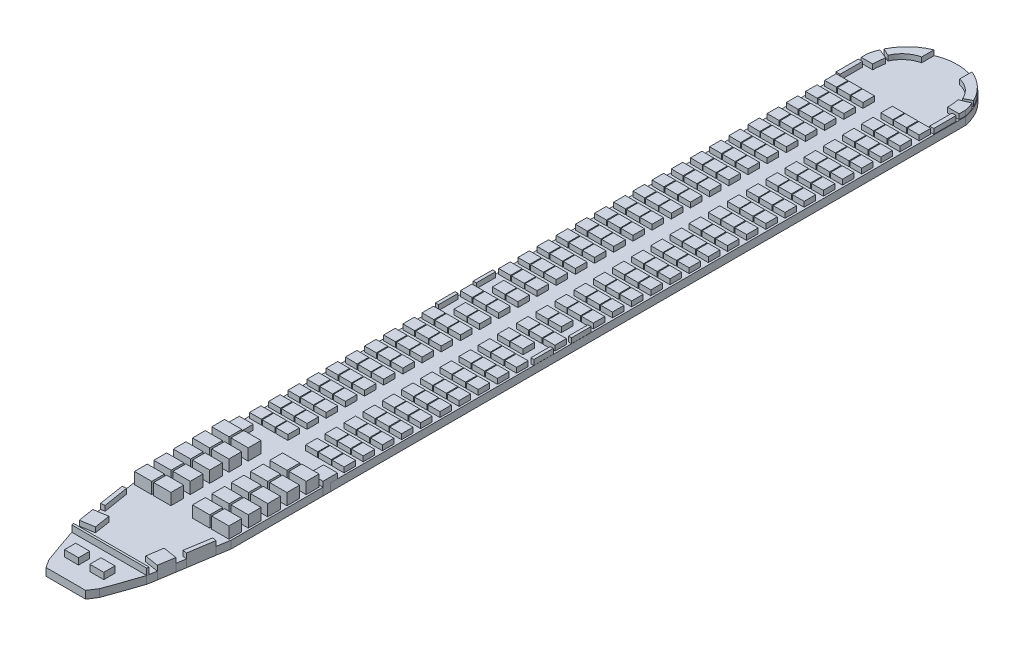
SolidWorks part; units mm, degrees
ref_plane "Front Plane" through (0, 0, 0) normal (0, 0, 1) x (1, 0, 0)
ref_plane "Top Plane" through (0, 0, 0) normal (0, 1, 0) x (1, 0, 0)
ref_plane "Right Plane" through (0, 0, 0) normal (1, 0, 0) x (0, 0, -1)
sketch "Sketch4" plane through (0, 0, 0) normal (0, 1, 0) x (1, 0, 0)
  line L0 (0, -18555.0286) -> (0, 12677.7658) construction
  line L1 (-353.06, -7443.1255) -> (-353.06, -6935.1255)
  line L2 (-861.06, -7443.1255) -> (-861.06, -6935.1255)
  line L3 (-1369.06, -7443.1255) -> (-1369.06, -6935.1255)
  line L4 (-788.8108, -16868.0938) -> (788.7905, -16868.1224)
  line L5 (-1877.0603, -7443.1255) -> (-1877.0603, -6935.1255)
  line L6 (1953.05, -7443.1255) -> (-1950.7053, -7443.1255)
  line L7 (279.4, -7443.1255) -> (279.4, 4976.8647)
  line L8 (-279.4, -7443.1255) -> (-279.4, 4976.8647)
  line L9 (-1950.6294, 16931.6309) -> (-1950.7203, -12251.7877)
  line L10 (1950.7203, -12251.7878) -> (1964.8593, 16931.6309)
  line L11 (-279.4, -6935.1255) -> (-1950.7037, -6935.1255)
  line L15 (-1950.6294, 18555.0286) -> (2313.12, 18555.0286)
  arc A0 (-1950.6294, 16931.6309) -> (1964.8593, 16931.6309) centre (7.1149, 16562.8541) cw
  spline S0 degree 3 poles (1488.5464, -15143.173) (1493.8408, -15113.3836) (1499.0901, -15083.5814) (1509.5061, -15023.9414) (1514.6725, -14994.1054) (1530.055, -14904.5516) (1540.1546, -14844.7882) (1570.0535, -14665.3302) (1589.4532, -14545.4685) (1646.5865, -14185.3284) (1683.256, -13944.4963) (1756.5726, -13461.8904) (1793.2205, -13220.1132) (1850.2435, -12857.1249) (1869.5925, -12736.0753) (1909.3095, -12493.9396) (1929.6777, -12372.8533) (1950.7203, -12251.7878) knots 0 0 0 0 0.03125 0.03125 0.0625 0.0625 0.125 0.125 0.25 0.25 0.5 0.5 0.75 0.75 0.875 0.875 1 1 1 1
  spline S1 degree 3 poles (999.9649, -16539.2617) (1005.4695, -16525.6191) (1010.9361, -16511.9298) (1021.7914, -16484.4765) (1027.1813, -16470.7098) (1043.2491, -16429.2828) (1053.8212, -16401.5056) (1074.7252, -16345.6545) (1085.0559, -16317.5842) (1105.5187, -16261.1657) (1115.6508, -16232.8175) (1135.7547, -16175.8725) (1145.7263, -16147.2766) (1165.5523, -16089.8535) (1175.4073, -16061.0243) (1195.0398, -16003.1622) (1204.8177, -15974.1278) (1224.3392, -15915.8705) (1234.0833, -15886.6465) (1263.3241, -15798.7288) (1282.832, -15739.7829) (1312.3584, -15650.9842) (1322.2446, -15621.3213) (1342.1443, -15561.8892) (1352.1573, -15532.1215) (1382.4464, -15442.6848) (1402.9709, -15382.8891) (1429.2239, -15308.0332) (1434.5042, -15293.0565) (1445.1288, -15263.0951) (1450.4726, -15248.1114) (1458.5409, -15225.6277) (1461.2401, -15218.1286) (1466.6541, -15203.1353) (1469.368, -15195.6434) (1477.5386, -15173.1613) (1483.0236, -15158.1667) (1488.5464, -15143.173) knots 0 0 0 0 0.03125 0.03125 0.0625 0.0625 0.125 0.125 0.1875 0.1875 0.25 0.25 0.3125 0.3125 0.375 0.375 0.4375 0.4375 0.5 0.5 0.625 0.625 0.6875 0.6875 0.75 0.75 0.875 0.875 0.90625 0.90625 0.9375 0.9375 0.953125 0.953125 0.96875 0.96875 1 1 1 1
  spline S2 degree 3 poles (788.7905, -16868.1224) (788.9402, -16867.912) (789.0761, -16867.7211) (789.259, -16867.464) (789.3175, -16867.3817) (789.4422, -16867.2064) (789.5069, -16867.1153) (789.8263, -16866.6658) (790.0788, -16866.3102) (790.836, -16865.2426) (791.3426, -16864.527) (792.8607, -16862.3784) (793.8711, -16860.9428) (796.9009, -16856.6218) (798.9185, -16853.7226) (804.9657, -16844.9703) (808.9896, -16839.0623) (821.0581, -16821.1093) (829.0989, -16808.8354) (845.2775, -16783.6501) (853.4149, -16770.7389) (869.8978, -16744.2812) (878.2431, -16730.7351) (895.2556, -16703.044) (903.9231, -16688.8991) (921.6924, -16660.0827) (930.7948, -16645.4108) (949.5378, -16615.6467) (959.1791, -16600.5541) (979.0872, -16570.0831) (989.3544, -16554.7048) (999.9649, -16539.2617) knots 0 0 0 0 0.001953 0.001953 0.00293 0.00293 0.003906 0.003906 0.007813 0.007813 0.015625 0.015625 0.03125 0.03125 0.0625 0.0625 0.125 0.125 0.25 0.25 0.375 0.375 0.5 0.5 0.625 0.625 0.75 0.75 0.875 0.875 1 1 1 1
  spline S3 degree 3 poles (-999.9649, -16539.2617) (-989.3542, -16554.7051) (-979.0871, -16570.0832) (-959.1793, -16600.5538) (-949.5381, -16615.6463) (-930.7946, -16645.4112) (-921.6925, -16660.0825) (-903.923, -16688.8992) (-895.2556, -16703.0441) (-878.2431, -16730.7351) (-869.8978, -16744.2812) (-853.4149, -16770.7389) (-845.2774, -16783.6501) (-829.099, -16808.8354) (-821.0581, -16821.1092) (-808.9895, -16839.0623) (-804.9656, -16844.9704) (-798.9186, -16853.7225) (-796.9011, -16856.6215) (-793.3659, -16861.6633) (-791.8492, -16863.8141) (-790.0778, -16866.3116) (-789.8247, -16866.6681) (-789.445, -16867.2025) (-789.2234, -16867.5141) (-789.0019, -16867.8254) (-788.8911, -16867.981) (-788.8752, -16868.0034) (-788.8438, -16868.0474) (-788.8295, -16868.0675) (-788.8108, -16868.0938) knots 0 0 0 0 0.125 0.125 0.25 0.25 0.375 0.375 0.5 0.5 0.625 0.625 0.75 0.75 0.875 0.875 0.9375 0.9375 0.96875 0.96875 0.992187 0.992187 0.996094 0.996094 0.998047 0.999512 0.999512 0.999756 0.999756 1 1 1 1
  spline S4 degree 3 poles (-1488.5464, -15143.173) (-1466.4555, -15203.1471) (-1444.9753, -15263.1205) (-1402.9707, -15382.8896) (-1382.4461, -15442.6857) (-1342.0613, -15561.9326) (-1322.2004, -15621.3853) (-1282.8319, -15739.783) (-1263.3238, -15798.7295) (-1234.083, -15886.6474) (-1224.3388, -15915.8717) (-1204.8176, -15974.128) (-1195.0399, -16003.162) (-1175.4071, -16061.0249) (-1165.552, -16089.8541) (-1145.7266, -16147.2758) (-1135.7546, -16175.8729) (-1105.5982, -16261.2916) (-1085.1766, -16317.7307) (-1053.8207, -16401.5068) (-1043.249, -16429.2832) (-1027.1814, -16470.7096) (-1021.7912, -16484.4771) (-1010.9348, -16511.933) (-1005.4692, -16525.6199) (-999.9649, -16539.2617) knots 0 0 0 0 0.125 0.125 0.25 0.25 0.375 0.375 0.5 0.5 0.5625 0.5625 0.625 0.625 0.6875 0.6875 0.75 0.75 0.875 0.875 0.9375 0.9375 0.96875 0.96875 1 1 1 1
  spline S5 degree 3 poles (-1950.7203, -12251.7877) (-1929.6774, -12372.8552) (-1909.3096, -12493.9394) (-1869.5925, -12736.0752) (-1850.2436, -12857.1248) (-1793.2205, -13220.1131) (-1756.5726, -13461.8903) (-1683.256, -13944.4963) (-1646.5865, -14185.3283) (-1589.4532, -14545.4685) (-1570.0535, -14665.3302) (-1530.1883, -14904.6075) (-1509.7227, -15024.0232) (-1488.5464, -15143.173) knots 0 0 0 0 0.125 0.125 0.25 0.25 0.5 0.5 0.75 0.75 0.875 0.875 1 1 1 1
extrude "Boss-Extrude3" add sketch "Sketch4" along normal blind 304.8 contours A0 L10 S0 S1 S2 L4 S3 S4 S5 L9
sketch "Sketch5" plane through (0, 304.8, 0) normal (0, 1, 0) x (1, 0, 0)
  line L0 (-1.9149, -18544.0824) -> (-1.9149, 12688.7119) construction
  line L1 (-354.9765, -7689.6055) -> (-354.9765, -7232.4055)
  line L2 (-862.9768, -7689.6055) -> (-862.9768, -7232.4055)
  line L3 (-1370.9768, -7689.6055) -> (-1370.9768, -7232.4055)
  line L4 (-792.6203, -16843.8865) -> (788.7905, -16868.1224)
  line L5 (-1878.9768, -7689.6055) -> (-1878.9768, -7232.4055)
  line L6 (1952.9306, -7689.6055) -> (-1952.6368, -7689.6055)
  line L7 (277.4851, -7689.6055) -> (277.4851, 4987.8108)
  line L8 (-281.3149, -7689.6055) -> (-281.3149, 4987.8108)
  line L9 (-1952.6368, 13195.4473) -> (-1952.6368, -12252.0947)
  line L10 (1950.7203, -12251.7878) -> (1951.6645, -10302.967)
  line L11 (-281.3149, -7232.4055) -> (-1952.6368, -7232.4055)
  line L12 (1951.6645, -10302.967) -> (1951.6645, 16988.1111)
  line L13 (-1944.822, 13189.6036) -> (-1944.822, 16948.92)
  line L14 (-366.7811, -10719.1073) -> (-1952.6368, -10719.1073)
  line L15 (-1116.9749, -9188.7614) -> (-1116.9749, -8680.7614)
  line L16 (-1878.9768, -6927.6055) -> (-1878.9768, -6470.4055)
  line L17 (-281.3149, -6470.4055) -> (-1952.6368, -6470.4055)
  line L18 (1952.9306, -6927.6055) -> (-1952.6368, -6927.6055)
  line L19 (-1370.9768, -6927.6055) -> (-1370.9768, -6470.4055)
  line L20 (-862.9768, -6927.6055) -> (-862.9768, -6470.4055)
  line L21 (-354.9765, -6927.6055) -> (-354.9765, -6470.4055)
  line L22 (-1878.9768, -6165.6055) -> (-1878.9768, -5708.4055)
  line L23 (-281.3149, -5708.4055) -> (-1952.6368, -5708.4055)
  line L24 (1952.9306, -6165.6055) -> (-1952.6368, -6165.6055)
  line L25 (-1370.9768, -6165.6055) -> (-1370.9768, -5708.4055)
  line L26 (-862.9768, -6165.6055) -> (-862.9768, -5708.4055)
  line L27 (-354.9765, -6165.6055) -> (-354.9765, -5708.4055)
  line L28 (-1878.9768, -5403.6055) -> (-1878.9768, -4946.4055)
  line L29 (-281.3149, -4946.4055) -> (-1952.6368, -4946.4055)
  line L30 (1952.9306, -5403.6055) -> (-1952.6368, -5403.6055)
  line L31 (-1370.9768, -5403.6055) -> (-1370.9768, -4946.4055)
  line L32 (-862.9768, -5403.6055) -> (-862.9768, -4946.4055)
  line L33 (-354.9765, -5403.6055) -> (-354.9765, -4946.4055)
  line L34 (-1878.9768, -4641.6055) -> (-1878.9768, -4184.4055)
  line L35 (-281.3149, -4184.4055) -> (-1952.6368, -4184.4055)
  line L36 (1952.9306, -4641.6055) -> (-1952.6368, -4641.6055)
  line L37 (-1370.9768, -4641.6055) -> (-1370.9768, -4184.4055)
  line L38 (-862.9768, -4641.6055) -> (-862.9768, -4184.4055)
  line L39 (-354.9765, -4641.6055) -> (-354.9765, -4184.4055)
  line L40 (-1878.9768, -3879.6055) -> (-1878.9768, -3422.4055)
  line L41 (-281.3149, -3422.4055) -> (-1952.6368, -3422.4055)
  line L42 (1952.9306, -3879.6055) -> (-1952.6368, -3879.6055)
  line L43 (-1370.9768, -3879.6055) -> (-1370.9768, -3422.4055)
  line L44 (-862.9768, -3879.6055) -> (-862.9768, -3422.4055)
  line L45 (-354.9765, -3879.6055) -> (-354.9765, -3422.4055)
  line L46 (-1878.9768, -3117.6055) -> (-1878.9768, -2660.4055)
  line L47 (-281.3149, -2660.4055) -> (-1952.6368, -2660.4055)
  line L48 (1952.9306, -3117.6055) -> (-1952.6368, -3117.6055)
  line L49 (-1370.9768, -3117.6055) -> (-1370.9768, -2660.4055)
  line L50 (-862.9768, -3117.6055) -> (-862.9768, -2660.4055)
  line L51 (-354.9765, -3117.6055) -> (-354.9765, -2660.4055)
  line L52 (-1878.9768, -2355.6055) -> (-1878.9768, -1898.4055)
  line L53 (-281.3149, -1898.4055) -> (-1952.6368, -1898.4055)
  line L54 (1952.9306, -2355.6055) -> (-1952.6368, -2355.6055)
  line L55 (-1370.9768, -2355.6055) -> (-1370.9768, -1898.4055)
  line L56 (-862.9768, -2355.6055) -> (-862.9768, -1898.4055)
  line L57 (-354.9765, -2355.6055) -> (-354.9765, -1898.4055)
  line L58 (-1878.9768, -1593.6055) -> (-1878.9768, -1136.4055)
  line L59 (-281.3149, -1136.4055) -> (-1952.6368, -1136.4055)
  line L60 (1952.9306, -1593.6055) -> (-1952.6368, -1593.6055)
  line L61 (-1370.9768, -1593.6055) -> (-1370.9768, -1136.4055)
  line L62 (-862.9768, -1593.6055) -> (-862.9768, -1136.4055)
  line L63 (-354.9765, -1593.6055) -> (-354.9765, -1136.4055)
  line L64 (-1878.9768, -831.6055) -> (-1878.9768, -374.4055)
  line L65 (-281.3149, -374.4055) -> (-1952.6368, -374.4055)
  line L66 (1952.9306, -831.6055) -> (-1952.6368, -831.6055)
  line L67 (-1370.9768, -831.6055) -> (-1370.9768, -374.4055)
  line L68 (-862.9768, -831.6055) -> (-862.9768, -374.4055)
  line L69 (-354.9765, -831.6055) -> (-354.9765, -374.4055)
  line L70 (1951.6645, 2049.5571) -> (1827.2312, 2049.5571)
  line L71 (-281.3149, 387.5945) -> (-1409.2609, 387.5945)
  line L72 (1952.9359, -69.6055) -> (1875.1469, -69.6055)
  line L73 (-1370.9768, -69.6055) -> (-1370.9768, 387.5945)
  line L74 (-862.9768, -69.6055) -> (-862.9768, 387.5945)
  line L75 (-354.9765, -69.6055) -> (-354.9765, 387.5945)
  line L76 (-1878.9768, 692.3945) -> (-1878.9768, 1149.5945)
  line L77 (-281.3149, 1149.5945) -> (-1952.6368, 1149.5945)
  line L78 (1952.9306, 692.3945) -> (-1952.6368, 692.3945)
  line L79 (-1370.9768, 692.3945) -> (-1370.9768, 1149.5945)
  line L80 (-862.9768, 692.3945) -> (-862.9768, 1149.5945)
  line L81 (-354.9765, 692.3945) -> (-354.9765, 1149.5945)
  line L82 (1827.2312, 2049.5571) -> (1827.2312, 1275.7694)
  line L83 (-281.3149, 1911.5945) -> (-1409.2609, 1911.5945)
  line L84 (1952.9359, 1454.3945) -> (1875.1469, 1454.3945)
  line L85 (-1370.9768, 1454.3945) -> (-1370.9768, 1911.5945)
  line L86 (-862.9768, 1454.3945) -> (-862.9768, 1911.5945)
  line L87 (-354.9765, 1454.3945) -> (-354.9765, 1911.5945)
  line L88 (-1878.9768, 2216.3945) -> (-1878.9768, 2673.5945)
  line L89 (-281.3149, 2673.5945) -> (-1409.2609, 2673.5945)
  line L90 (1952.9359, 2216.3945) -> (-1409.2609, 2216.3945)
  line L91 (-1370.9768, 2216.3945) -> (-1370.9768, 2673.5945)
  line L92 (-862.9768, 2216.3945) -> (-862.9768, 2673.5945)
  line L93 (-354.9765, 2216.3945) -> (-354.9765, 2673.5945)
  line L94 (-1878.9768, 2978.3945) -> (-1878.9768, 3435.5945)
  line L95 (-281.3149, 3435.5945) -> (-1952.6368, 3435.5945)
  line L96 (1952.9306, 2978.3945) -> (-1952.6368, 2978.3945)
  line L97 (-1370.9768, 2978.3945) -> (-1370.9768, 3435.5945)
  line L98 (-862.9768, 2978.3945) -> (-862.9768, 3435.5945)
  line L99 (-354.9765, 2978.3945) -> (-354.9765, 3435.5945)
  line L100 (-1878.9768, 3740.3945) -> (-1878.9768, 4197.5945)
  line L101 (-281.3149, 4197.5945) -> (-1952.6368, 4197.5945)
  line L102 (1952.9306, 3740.3945) -> (-1952.6368, 3740.3945)
  line L103 (-1370.9768, 3740.3945) -> (-1370.9768, 4197.5945)
  line L104 (-862.9768, 3740.3945) -> (-862.9768, 4197.5945)
  line L105 (-354.9765, 3740.3945) -> (-354.9765, 4197.5945)
  line L106 (-1878.9768, 4502.3945) -> (-1878.9768, 4959.5945)
  line L107 (-281.3149, 4959.5945) -> (-1952.6368, 4959.5945)
  line L108 (1952.9306, 4502.3945) -> (-1952.6368, 4502.3945)
  line L109 (-1370.9768, 4502.3945) -> (-1370.9768, 4959.5945)
  line L110 (-862.9768, 4502.3945) -> (-862.9768, 4959.5945)
  line L111 (-354.9765, 4502.3945) -> (-354.9765, 4959.5945)
  line L112 (-1878.9768, 5264.3945) -> (-1878.9768, 5721.5945)
  line L113 (-281.3149, 5721.5945) -> (-1952.6368, 5721.5945)
  line L114 (1952.9306, 5264.3945) -> (-1952.6368, 5264.3945)
  line L115 (-1370.9768, 5264.3945) -> (-1370.9768, 5721.5945)
  line L116 (-862.9768, 5264.3945) -> (-862.9768, 5721.5945)
  line L117 (-354.9765, 5264.3945) -> (-354.9765, 5721.5945)
  line L118 (-1878.9768, 6026.3945) -> (-1878.9768, 6483.5945)
  line L119 (-281.3149, 6483.5945) -> (-1952.6368, 6483.5945)
  line L120 (1952.9306, 6026.3945) -> (-1952.6368, 6026.3945)
  line L121 (-1370.9768, 6026.3945) -> (-1370.9768, 6483.5945)
  line L122 (-862.9768, 6026.3945) -> (-862.9768, 6483.5945)
  line L123 (-354.9765, 6026.3945) -> (-354.9765, 6483.5945)
  line L124 (-1878.9768, 6788.3945) -> (-1878.9768, 7245.5945)
  line L125 (-281.3149, 7245.5945) -> (-1952.6368, 7245.5945)
  line L126 (1952.9306, 6788.3945) -> (-1952.6368, 6788.3945)
  line L127 (-1370.9768, 6788.3945) -> (-1370.9768, 7245.5945)
  line L128 (-862.9768, 6788.3945) -> (-862.9768, 7245.5945)
  line L129 (-354.9765, 6788.3945) -> (-354.9765, 7245.5945)
  line L130 (-1878.9768, 7550.3945) -> (-1878.9768, 8007.5945)
  line L131 (-281.3149, 8007.5945) -> (-1952.6368, 8007.5945)
  line L132 (1952.9306, 7550.3945) -> (-1952.6368, 7550.3945)
  line L133 (-1370.9768, 7550.3945) -> (-1370.9768, 8007.5945)
  line L134 (-862.9768, 7550.3945) -> (-862.9768, 8007.5945)
  line L135 (-354.9765, 7550.3945) -> (-354.9765, 8007.5945)
  line L136 (-1878.9768, 8312.3945) -> (-1878.9768, 8769.5945)
  line L137 (-281.3149, 8769.5945) -> (-1952.6368, 8769.5945)
  line L138 (1952.9306, 8312.3945) -> (-1952.6368, 8312.3945)
  line L139 (-1370.9768, 8312.3945) -> (-1370.9768, 8769.5945)
  line L140 (-862.9768, 8312.3945) -> (-862.9768, 8769.5945)
  line L141 (-354.9765, 8312.3945) -> (-354.9765, 8769.5945)
  line L142 (-1878.9768, 9074.3945) -> (-1878.9768, 9531.5945)
  line L143 (-281.3149, 9531.5945) -> (-1952.6368, 9531.5945)
  line L144 (1952.9306, 9074.3945) -> (-1952.6368, 9074.3945)
  line L145 (-1370.9768, 9074.3945) -> (-1370.9768, 9531.5945)
  line L146 (-862.9768, 9074.3945) -> (-862.9768, 9531.5945)
  line L147 (-354.9765, 9074.3945) -> (-354.9765, 9531.5945)
  line L148 (-1878.9768, 9836.3945) -> (-1878.9768, 10293.5945)
  line L149 (-281.3149, 10293.5945) -> (-1952.6368, 10293.5945)
  line L150 (1952.9306, 9836.3945) -> (-1952.6368, 9836.3945)
  line L151 (-1370.9768, 9836.3945) -> (-1370.9768, 10293.5945)
  line L152 (-862.9768, 9836.3945) -> (-862.9768, 10293.5945)
  line L153 (-354.9765, 9836.3945) -> (-354.9765, 10293.5945)
  line L154 (-1878.9768, 10598.3945) -> (-1878.9768, 11055.5945)
  line L155 (-281.3149, 11055.5945) -> (-1952.6368, 11055.5945)
  line L156 (1952.9306, 10598.3945) -> (-1952.6368, 10598.3945)
  line L157 (-1370.9768, 10598.3945) -> (-1370.9768, 11055.5945)
  line L158 (-862.9768, 10598.3945) -> (-862.9768, 11055.5945)
  line L159 (-354.9765, 10598.3945) -> (-354.9765, 11055.5945)
  line L160 (-1878.9768, 11360.3945) -> (-1878.9768, 11817.5945)
  line L161 (-281.3149, 11817.5945) -> (-1952.6368, 11817.5945)
  line L162 (1952.9306, 11360.3945) -> (-1952.6368, 11360.3945)
  line L163 (-1370.9768, 11360.3945) -> (-1370.9768, 11817.5945)
  line L164 (-862.9768, 11360.3945) -> (-862.9768, 11817.5945)
  line L165 (-354.9765, 11360.3945) -> (-354.9765, 11817.5945)
  line L166 (-1878.9768, 12122.3945) -> (-1878.9768, 12579.5945)
  line L167 (-281.3149, 12579.5945) -> (-1952.6368, 12579.5945)
  line L168 (1952.9306, 12122.3945) -> (-1952.6368, 12122.3945)
  line L169 (-1370.9768, 12122.3945) -> (-1370.9768, 12579.5945)
  line L170 (-862.9768, 12122.3945) -> (-862.9768, 12579.5945)
  line L171 (-354.9765, 12122.3945) -> (-354.9765, 12579.5945)
  line L172 (-1878.9768, 12884.3945) -> (-1878.9768, 13341.5945)
  line L173 (-281.3149, 13341.5945) -> (-1952.6368, 13341.5945)
  line L174 (1952.9306, 12884.3945) -> (-1952.6368, 12884.3945)
  line L175 (-1370.9768, 12884.3945) -> (-1370.9768, 13341.5945)
  line L176 (-862.9768, 12884.3945) -> (-862.9768, 13341.5945)
  line L177 (-354.9765, 12884.3945) -> (-354.9765, 13341.5945)
  line L178 (-1878.9768, 13646.3945) -> (-1878.9768, 14103.5945)
  line L179 (-281.3149, 14103.5945) -> (-1952.6368, 14103.5945)
  line L180 (1952.9306, 13646.3945) -> (-1952.6368, 13646.3945)
  line L181 (-1370.9768, 13646.3945) -> (-1370.9768, 14103.5945)
  line L182 (-862.9768, 13646.3945) -> (-862.9768, 14103.5945)
  line L183 (-354.9765, 13646.3945) -> (-354.9765, 14103.5945)
  line L184 (-1878.9768, 14408.3945) -> (-1878.9768, 14865.5945)
  line L185 (-281.3149, 14865.5945) -> (-1952.6368, 14865.5945)
  line L186 (1952.9306, 14408.3945) -> (-1952.6368, 14408.3945)
  line L187 (-1370.9768, 14408.3945) -> (-1370.9768, 14865.5945)
  line L188 (-862.9768, 14408.3945) -> (-862.9768, 14865.5945)
  line L189 (-354.9765, 14408.3945) -> (-354.9765, 14865.5945)
  line L190 (-1878.9768, 15170.3945) -> (-1878.9768, 15627.5945)
  line L191 (-281.3149, 15627.5945) -> (-1952.6368, 15627.5945)
  line L192 (1952.9306, 15170.3945) -> (-1952.6368, 15170.3945)
  line L193 (-1370.9768, 15170.3945) -> (-1370.9768, 15627.5945)
  line L194 (-862.9768, 15170.3945) -> (-862.9768, 15627.5945)
  line L195 (-354.9765, 15170.3945) -> (-354.9765, 15627.5945)
  line L196 (1950.7203, -12251.7878) -> (1807.9213, -13127.5335)
  line L197 (1807.9213, -13127.5335) -> (1540.9739, -13084.0051)
  line L198 (-357.5149, -9186.3576) -> (-357.5149, -12251.8569)
  line L199 (353.6851, -9186.3576) -> (353.6851, -12251.8569)
  line L200 (-281.3131, -8680.7614) -> (-1952.6368, -8680.7614)
  line L201 (-281.3131, -9188.7614) -> (-1952.6368, -9188.7614)
  line L202 (-431.1749, -8680.7614) -> (-431.1749, -9188.7614)
  line L203 (1488.5464, -15143.173) -> (-1488.5464, -15143.173)
  line L204 (1950.7203, -12251.7878) -> (1964.8593, 16931.6309) construction
  line L205 (-1878.9768, -8680.7614) -> (-1878.9768, -9188.7614)
  line L206 (-281.3131, -9448.7135) -> (-1952.6368, -9448.7135)
  line L207 (-431.1749, -9448.7135) -> (-431.1749, -9956.7135)
  line L208 (-1116.9749, -9956.7135) -> (-1116.9749, -9448.7135)
  line L209 (-1878.9768, -9448.7135) -> (-1878.9768, -9956.7135)
  line L210 (-281.3131, -9956.7135) -> (-1952.6368, -9956.7135)
  line L211 (-281.3131, -10216.6657) -> (-1952.6368, -10216.6657)
  line L212 (-431.1749, -10216.6657) -> (-431.1749, -10724.6657)
  line L213 (-1116.9749, -10724.6657) -> (-1116.9749, -10216.6657)
  line L214 (-1878.9768, -10216.6657) -> (-1878.9768, -10724.6657)
  line L215 (-281.3131, -10724.6657) -> (-1952.6368, -10724.6657)
  line L216 (-281.3131, -10984.6178) -> (-1952.6368, -10984.6178)
  line L217 (-431.1749, -10984.6178) -> (-431.1749, -11492.6178)
  line L218 (-1116.9749, -11492.6178) -> (-1116.9749, -10984.6178)
  line L219 (-1878.9768, -10984.6178) -> (-1878.9768, -11492.6178)
  line L220 (-281.3131, -11492.6178) -> (-1952.6368, -11492.6178)
  line L221 (-281.3131, -11752.5699) -> (-1952.6368, -11752.5699)
  line L222 (-431.1749, -11752.5699) -> (-431.1749, -12260.5699)
  line L223 (-1116.9749, -12260.5699) -> (-1116.9749, -11752.5699)
  line L224 (-1878.9768, -11752.5699) -> (-1878.9768, -12260.5699)
  line L225 (-281.3131, -12260.5699) -> (-1952.6368, -12260.5699)
  line L226 (-1193.1768, -8680.7614) -> (-1193.1768, -12260.5699)
  line L227 (-832.6383, 15627.5945) -> (-832.6383, -7689.6055)
  line L228 (-1409.2609, 15627.5945) -> (-1409.2609, -7689.6055)
  line L229 (1405.4311, 15627.5945) -> (1405.4311, -7689.6055)
  line L230 (828.8085, 15627.5945) -> (828.8085, -7689.6055)
  line L231 (351.1467, 15170.3945) -> (351.1467, 15627.5945)
  line L232 (859.1469, 15170.3945) -> (859.1469, 15627.5945)
  line L233 (1367.1469, 15170.3945) -> (1367.1469, 15627.5945)
  line L234 (277.4851, 15627.5945) -> (1948.8069, 15627.5945)
  line L235 (1875.1469, 15170.3945) -> (1875.1469, 15627.5945)
  line L236 (351.1467, 14408.3945) -> (351.1467, 14865.5945)
  line L237 (859.1469, 14408.3945) -> (859.1469, 14865.5945)
  line L238 (1367.1469, 14408.3945) -> (1367.1469, 14865.5945)
  line L239 (277.4851, 14865.5945) -> (1948.8069, 14865.5945)
  line L240 (1875.1469, 14408.3945) -> (1875.1469, 14865.5945)
  line L241 (351.1467, 13646.3945) -> (351.1467, 14103.5945)
  line L242 (859.1469, 13646.3945) -> (859.1469, 14103.5945)
  line L243 (1367.1469, 13646.3945) -> (1367.1469, 14103.5945)
  line L244 (277.4851, 14103.5945) -> (1948.8069, 14103.5945)
  line L245 (1875.1469, 13646.3945) -> (1875.1469, 14103.5945)
  line L246 (351.1467, 12884.3945) -> (351.1467, 13341.5945)
  line L247 (859.1469, 12884.3945) -> (859.1469, 13341.5945)
  line L248 (1367.1469, 12884.3945) -> (1367.1469, 13341.5945)
  line L249 (277.4851, 13341.5945) -> (1948.8069, 13341.5945)
  line L250 (1875.1469, 12884.3945) -> (1875.1469, 13341.5945)
  line L251 (351.1467, 12122.3945) -> (351.1467, 12579.5945)
  line L252 (859.1469, 12122.3945) -> (859.1469, 12579.5945)
  line L253 (1367.1469, 12122.3945) -> (1367.1469, 12579.5945)
  line L254 (277.4851, 12579.5945) -> (1948.8069, 12579.5945)
  line L255 (1875.1469, 12122.3945) -> (1875.1469, 12579.5945)
  line L256 (351.1467, 11360.3945) -> (351.1467, 11817.5945)
  line L257 (859.1469, 11360.3945) -> (859.1469, 11817.5945)
  line L258 (1367.1469, 11360.3945) -> (1367.1469, 11817.5945)
  line L259 (277.4851, 11817.5945) -> (1948.8069, 11817.5945)
  line L260 (1875.1469, 11360.3945) -> (1875.1469, 11817.5945)
  line L261 (351.1467, 10598.3945) -> (351.1467, 11055.5945)
  line L262 (859.1469, 10598.3945) -> (859.1469, 11055.5945)
  line L263 (1367.1469, 10598.3945) -> (1367.1469, 11055.5945)
  line L264 (277.4851, 11055.5945) -> (1948.8069, 11055.5945)
  line L265 (1875.1469, 10598.3945) -> (1875.1469, 11055.5945)
  line L266 (351.1467, 9836.3945) -> (351.1467, 10293.5945)
  line L267 (859.1469, 9836.3945) -> (859.1469, 10293.5945)
  line L268 (1367.1469, 9836.3945) -> (1367.1469, 10293.5945)
  line L269 (277.4851, 10293.5945) -> (1948.8069, 10293.5945)
  line L270 (1875.1469, 9836.3945) -> (1875.1469, 10293.5945)
  line L271 (351.1467, 9074.3945) -> (351.1467, 9531.5945)
  line L272 (859.1469, 9074.3945) -> (859.1469, 9531.5945)
  line L273 (1367.1469, 9074.3945) -> (1367.1469, 9531.5945)
  line L274 (277.4851, 9531.5945) -> (1948.8069, 9531.5945)
  line L275 (1875.1469, 9074.3945) -> (1875.1469, 9531.5945)
  line L276 (351.1467, 8312.3945) -> (351.1467, 8769.5945)
  line L277 (859.1469, 8312.3945) -> (859.1469, 8769.5945)
  line L278 (1367.1469, 8312.3945) -> (1367.1469, 8769.5945)
  line L279 (277.4851, 8769.5945) -> (1948.8069, 8769.5945)
  line L280 (1875.1469, 8312.3945) -> (1875.1469, 8769.5945)
  line L281 (351.1467, 7550.3945) -> (351.1467, 8007.5945)
  line L282 (859.1469, 7550.3945) -> (859.1469, 8007.5945)
  line L283 (1367.1469, 7550.3945) -> (1367.1469, 8007.5945)
  line L284 (277.4851, 8007.5945) -> (1948.8069, 8007.5945)
  line L285 (1875.1469, 7550.3945) -> (1875.1469, 8007.5945)
  line L286 (351.1467, 6788.3945) -> (351.1467, 7245.5945)
  line L287 (859.1469, 6788.3945) -> (859.1469, 7245.5945)
  line L288 (1367.1469, 6788.3945) -> (1367.1469, 7245.5945)
  line L289 (277.4851, 7245.5945) -> (1948.8069, 7245.5945)
  line L290 (1875.1469, 6788.3945) -> (1875.1469, 7245.5945)
  line L291 (351.1467, 6026.3945) -> (351.1467, 6483.5945)
  line L292 (859.1469, 6026.3945) -> (859.1469, 6483.5945)
  line L293 (1367.1469, 6026.3945) -> (1367.1469, 6483.5945)
  line L294 (277.4851, 6483.5945) -> (1948.8069, 6483.5945)
  line L295 (1875.1469, 6026.3945) -> (1875.1469, 6483.5945)
  line L296 (351.1467, 5264.3945) -> (351.1467, 5721.5945)
  line L297 (859.1469, 5264.3945) -> (859.1469, 5721.5945)
  line L298 (1367.1469, 5264.3945) -> (1367.1469, 5721.5945)
  line L299 (277.4851, 5721.5945) -> (1948.8069, 5721.5945)
  line L300 (1875.1469, 5264.3945) -> (1875.1469, 5721.5945)
  line L301 (351.1467, 4502.3945) -> (351.1467, 4959.5945)
  line L302 (859.1469, 4502.3945) -> (859.1469, 4959.5945)
  line L303 (1367.1469, 4502.3945) -> (1367.1469, 4959.5945)
  line L304 (277.4851, 4959.5945) -> (1948.8069, 4959.5945)
  line L305 (1875.1469, 4502.3945) -> (1875.1469, 4959.5945)
  line L306 (351.1467, 3740.3945) -> (351.1467, 4197.5945)
  line L307 (859.1469, 3740.3945) -> (859.1469, 4197.5945)
  line L308 (1367.1469, 3740.3945) -> (1367.1469, 4197.5945)
  line L309 (277.4851, 4197.5945) -> (1948.8069, 4197.5945)
  line L310 (1875.1469, 3740.3945) -> (1875.1469, 4197.5945)
  line L311 (351.1467, 2978.3945) -> (351.1467, 3435.5945)
  line L312 (859.1469, 2978.3945) -> (859.1469, 3435.5945)
  line L313 (1367.1469, 2978.3945) -> (1367.1469, 3435.5945)
  line L314 (277.4851, 3435.5945) -> (1948.8069, 3435.5945)
  line L315 (1875.1469, 2978.3945) -> (1875.1469, 3435.5945)
  line L316 (351.1467, 2216.3945) -> (351.1467, 2673.5945)
  line L317 (859.1469, 2216.3945) -> (859.1469, 2673.5945)
  line L318 (1367.1469, 2216.3945) -> (1367.1469, 2673.5945)
  line L319 (277.4851, 2673.5945) -> (1948.8069, 2673.5945)
  line L320 (1875.1469, 2216.3945) -> (1875.1469, 2673.5945)
  line L321 (351.1467, 1454.3945) -> (351.1467, 1911.5945)
  line L322 (859.1469, 1454.3945) -> (859.1469, 1911.5945)
  line L323 (1367.1469, 1454.3945) -> (1367.1469, 1911.5945)
  line L324 (277.4851, 1911.5945) -> (1405.4311, 1911.5945)
  line L325 (1827.2312, 1275.7694) -> (1951.6645, 1275.7694)
  line L326 (351.1467, 692.3945) -> (351.1467, 1149.5945)
  line L327 (859.1469, 692.3945) -> (859.1469, 1149.5945)
  line L328 (1367.1469, 692.3945) -> (1367.1469, 1149.5945)
  line L329 (277.4851, 1149.5945) -> (1948.8069, 1149.5945)
  line L330 (1875.1469, 692.3945) -> (1875.1469, 1149.5945)
  line L331 (351.1467, -69.6055) -> (351.1467, 387.5945)
  line L332 (859.1469, -69.6055) -> (859.1469, 387.5945)
  line L333 (1367.1469, -69.6055) -> (1367.1469, 387.5945)
  line L334 (277.4851, 387.5945) -> (1405.4311, 387.5945)
  line L335 (1827.2312, 554.001) -> (1827.2312, -219.7868)
  line L336 (351.1467, -831.6055) -> (351.1467, -374.4055)
  line L337 (859.1469, -831.6055) -> (859.1469, -374.4055)
  line L338 (1367.1469, -831.6055) -> (1367.1469, -374.4055)
  line L339 (277.4851, -374.4055) -> (1948.8069, -374.4055)
  line L340 (1875.1469, -831.6055) -> (1875.1469, -374.4055)
  line L341 (351.1467, -1593.6055) -> (351.1467, -1136.4055)
  line L342 (859.1469, -1593.6055) -> (859.1469, -1136.4055)
  line L343 (1367.1469, -1593.6055) -> (1367.1469, -1136.4055)
  line L344 (277.4851, -1136.4055) -> (1948.8069, -1136.4055)
  line L345 (1875.1469, -1593.6055) -> (1875.1469, -1136.4055)
  line L346 (351.1467, -2355.6055) -> (351.1467, -1898.4055)
  line L347 (859.1469, -2355.6055) -> (859.1469, -1898.4055)
  line L348 (1367.1469, -2355.6055) -> (1367.1469, -1898.4055)
  line L349 (277.4851, -1898.4055) -> (1948.8069, -1898.4055)
  line L350 (1875.1469, -2355.6055) -> (1875.1469, -1898.4055)
  line L351 (351.1467, -3117.6055) -> (351.1467, -2660.4055)
  line L352 (859.1469, -3117.6055) -> (859.1469, -2660.4055)
  line L353 (1367.1469, -3117.6055) -> (1367.1469, -2660.4055)
  line L354 (277.4851, -2660.4055) -> (1948.8069, -2660.4055)
  line L355 (1875.1469, -3117.6055) -> (1875.1469, -2660.4055)
  line L356 (351.1467, -3879.6055) -> (351.1467, -3422.4055)
  line L357 (859.1469, -3879.6055) -> (859.1469, -3422.4055)
  line L358 (1367.1469, -3879.6055) -> (1367.1469, -3422.4055)
  line L359 (277.4851, -3422.4055) -> (1948.8069, -3422.4055)
  line L360 (1875.1469, -3879.6055) -> (1875.1469, -3422.4055)
  line L361 (351.1467, -4641.6055) -> (351.1467, -4184.4055)
  line L362 (859.1469, -4641.6055) -> (859.1469, -4184.4055)
  line L363 (1367.1469, -4641.6055) -> (1367.1469, -4184.4055)
  line L364 (277.4851, -4184.4055) -> (1948.8069, -4184.4055)
  line L365 (1875.1469, -4641.6055) -> (1875.1469, -4184.4055)
  line L366 (351.1467, -5403.6055) -> (351.1467, -4946.4055)
  line L367 (859.1469, -5403.6055) -> (859.1469, -4946.4055)
  line L368 (1367.1469, -5403.6055) -> (1367.1469, -4946.4055)
  line L369 (277.4851, -4946.4055) -> (1948.8069, -4946.4055)
  line L370 (1875.1469, -5403.6055) -> (1875.1469, -4946.4055)
  line L371 (351.1467, -6165.6055) -> (351.1467, -5708.4055)
  line L372 (859.1469, -6165.6055) -> (859.1469, -5708.4055)
  line L373 (1367.1469, -6165.6055) -> (1367.1469, -5708.4055)
  line L374 (277.4851, -5708.4055) -> (1948.8069, -5708.4055)
  line L375 (1875.1469, -6165.6055) -> (1875.1469, -5708.4055)
  line L376 (351.1467, -6927.6055) -> (351.1467, -6470.4055)
  line L377 (859.1469, -6927.6055) -> (859.1469, -6470.4055)
  line L378 (1367.1469, -6927.6055) -> (1367.1469, -6470.4055)
  line L379 (277.4851, -6470.4055) -> (1948.8069, -6470.4055)
  line L380 (1875.1469, -6927.6055) -> (1875.1469, -6470.4055)
  line L381 (277.4851, -7232.4055) -> (1948.8069, -7232.4055)
  line L382 (277.4851, -7689.6055) -> (277.4851, 4987.8108)
  line L383 (-281.3149, -7689.6055) -> (-281.3149, 4987.8108)
  line L384 (1875.1469, -7689.6055) -> (1875.1469, -7232.4055)
  line L385 (1367.1469, -7689.6055) -> (1367.1469, -7232.4055)
  line L386 (859.1469, -7689.6055) -> (859.1469, -7232.4055)
  line L387 (351.1467, -7689.6055) -> (351.1467, -7232.4055)
  line L388 (-1944.822, 16573.1561) -> (-1781.8952, 16573.1561)
  line L389 (-1781.8952, 16573.1561) -> (-1781.8952, 15684.1561)
  line L390 (-1781.8952, 15684.1561) -> (-1944.822, 15684.1561)
  line L391 (-1944.822, 16690.8235) -> (-1487.3768, 16690.8235)
  line L392 (-1831.061, 17319.4156) -> (-1441.0463, 17156.6623)
  line L393 (1484.7165, 17290.3073) -> (1775.2729, 17433.6613)
  line L394 (-756.5521, 18392.1053) -> (-756.5521, 17904.3161)
  line L395 (-756.5521, 17904.3161) -> (-4.3843, 17904.3161)
  line L396 (-1488.5464, 17290.3073) -> (-1779.1028, 17433.6613)
  line L397 (752.7223, 17904.3161) -> (0.5544, 17904.3161)
  line L398 (752.7223, 18392.1053) -> (752.7223, 17904.3161)
  line L399 (1775.2729, 17433.6613) -> (1484.7165, 17290.3073)
  line L400 (1778.0653, 15684.1561) -> (1940.9921, 15684.1561)
  line L401 (1778.0653, 16573.1561) -> (1778.0653, 15684.1561)
  line L402 (1940.9921, 16573.1561) -> (1778.0653, 16573.1561)
  line L403 (1940.9921, 16690.8235) -> (1483.5469, 16690.8235)
  line L404 (-1952.6368, -8023.9566) -> (-1397.4899, -8023.9566)
  line L405 (-1397.4899, -8023.9566) -> (-1397.4899, -8598.5137)
  line L406 (-1397.4899, -8598.5137) -> (-1952.6368, -8598.5137)
  line L407 (1393.6601, -8598.5137) -> (1948.8069, -8598.5137)
  line L408 (1393.6601, -8023.9566) -> (1393.6601, -8598.5137)
  line L409 (1948.8069, -8023.9566) -> (1393.6601, -8023.9566)
  line L410 (-1866.5709, -12765.8723) -> (-1710.4623, -12740.6632)
  line L411 (-1710.4623, -12740.6632) -> (-1546.1162, -13758.385)
  line L412 (-1546.1162, -13758.385) -> (-1708.6762, -13783.2153)
  line L413 (-1652.9369, -14145.7351) -> (-1096.9964, -14059.4126)
  line L414 (-1096.9964, -14059.4126) -> (-998.796, -14691.8497)
  line L415 (-998.796, -14691.8497) -> (-1550.5053, -14784.1312)
  line L416 (1827.2312, 17319.4156) -> (1437.2165, 17156.6623)
  line L417 (-1878.9768, 2673.5945) -> (-1952.6368, 2673.5945)
  line L418 (-1878.9768, 2216.3945) -> (-1952.6368, 2216.3945)
  line L419 (-1878.9768, 387.5945) -> (-1952.6368, 387.5945)
  line L420 (-1878.9768, -69.6055) -> (-1952.6368, -69.6055)
  line L421 (-1878.9768, 1911.5945) -> (-1952.6368, 1911.5945)
  line L422 (-1878.9768, 1454.3945) -> (-1952.6368, 1454.3945)
  line L423 (-1878.9768, 2673.5945) -> (-1409.2609, 2673.5945)
  line L424 (-1370.9768, 2216.3945) -> (-1878.9768, 2216.3945)
  line L425 (1875.1469, 1911.5945) -> (1948.8069, 1911.5945)
  line L426 (1405.4311, 1454.3945) -> (-1409.2609, 1454.3945)
  line L427 (1875.1469, 387.5945) -> (1948.8069, 387.5945)
  line L428 (1405.4311, -69.6055) -> (-1409.2609, -69.6055)
  line L429 (-1878.9768, 1454.3945) -> (-1878.9768, 1911.5945) [skipped]
  line L430 (-1878.9768, -69.6055) -> (-1878.9768, 387.5945) [skipped]
  line L431 (1951.6645, 554.001) -> (1827.2312, 554.001)
  line L432 (1827.2312, -219.7868) -> (1951.6645, -219.7868)
  line L433 (-1831.061, -219.7868) -> (-1955.4943, -219.7868)
  line L434 (-1831.061, 554.001) -> (-1831.061, -219.7868)
  line L435 (-1955.4943, 554.001) -> (-1831.061, 554.001)
  line L436 (-1955.4943, 2049.5571) -> (-1831.061, 2049.5571)
  line L437 (-1831.061, 1275.7694) -> (-1955.4943, 1275.7694)
  line L438 (-1831.061, 2049.5571) -> (-1831.061, 1275.7694)
  line L439 (994.9662, -14691.8497) -> (1546.6754, -14784.1312)
  line L440 (1093.1665, -14059.4126) -> (994.9662, -14691.8497)
  line L441 (1649.107, -14145.7351) -> (1093.1665, -14059.4126)
  line L442 (1542.2863, -13758.385) -> (1704.8463, -13783.2153)
  line L443 (1706.6325, -12740.6632) -> (1542.2863, -13758.385)
  line L444 (1862.741, -12765.8723) -> (1706.6325, -12740.6632)
  line L445 (1393.6601, -8598.5137) -> (1948.8069, -8598.5137)
  line L446 (1189.3469, -8680.7614) -> (1189.3469, -12260.5699)
  line L447 (277.4832, -12260.5699) -> (1948.8069, -12260.5699)
  line L448 (1875.1469, -11752.5699) -> (1875.1469, -12260.5699)
  line L449 (1113.1451, -12260.5699) -> (1113.1451, -11752.5699)
  line L450 (427.3451, -11752.5699) -> (427.3451, -12260.5699)
  line L451 (277.4832, -11752.5699) -> (1948.8069, -11752.5699)
  line L452 (277.4832, -11492.6178) -> (1948.8069, -11492.6178)
  line L453 (1875.1469, -10984.6178) -> (1875.1469, -11492.6178)
  line L454 (1113.1451, -11492.6178) -> (1113.1451, -10984.6178)
  line L455 (427.3451, -10984.6178) -> (427.3451, -11492.6178)
  line L456 (277.4832, -10984.6178) -> (1948.8069, -10984.6178)
  line L457 (277.4832, -10724.6657) -> (1948.8069, -10724.6657)
  line L458 (1875.1469, -10216.6657) -> (1875.1469, -10724.6657)
  line L459 (1113.1451, -10724.6657) -> (1113.1451, -10216.6657)
  line L460 (427.3451, -10216.6657) -> (427.3451, -10724.6657)
  line L461 (277.4832, -10216.6657) -> (1948.8069, -10216.6657)
  line L462 (277.4832, -9956.7135) -> (1948.8069, -9956.7135)
  line L463 (1875.1469, -9448.7135) -> (1875.1469, -9956.7135)
  line L464 (1113.1451, -9956.7135) -> (1113.1451, -9448.7135)
  line L465 (427.3451, -9448.7135) -> (427.3451, -9956.7135)
  line L466 (277.4832, -9448.7135) -> (1948.8069, -9448.7135)
  line L467 (1875.1469, -8680.7614) -> (1875.1469, -9188.7614)
  line L468 (427.3451, -8680.7614) -> (427.3451, -9188.7614)
  line L469 (277.4832, -9188.7614) -> (1948.8069, -9188.7614)
  line L470 (277.4832, -8680.7614) -> (1948.8069, -8680.7614)
  line L471 (353.6851, -9186.3576) -> (353.6851, -12251.8569)
  line L472 (1113.1451, -9188.7614) -> (1113.1451, -8680.7614)
  line L473 (362.9513, -10719.1073) -> (1948.8069, -10719.1073)
  arc A0 (1951.6645, 16988.1111) -> (-1944.822, 16948.92) centre (7.6092, 16552.1376) ccw
  arc A1 (-1488.5464, 17290.3073) -> (-756.5521, 17904.3161) centre (-510.5952, 16867.7669) cw
  arc A2 (1484.7165, 17290.3073) -> (752.7223, 17904.3161) centre (506.7653, 16867.7669) ccw
  arc A3 (-1441.0463, 17156.6623) -> (-1487.3768, 16690.8235) centre (1160.4734, 16662.7021) ccw
  arc A4 (1437.2165, 17156.6623) -> (1483.5469, 16690.8235) centre (-1164.3033, 16662.7021) cw
  spline S0 degree 3 poles (1488.5464, -15143.173) (1493.8408, -15113.3836) (1499.0901, -15083.5814) (1509.5061, -15023.9414) (1514.6725, -14994.1054) (1530.055, -14904.5516) (1540.1546, -14844.7882) (1570.0535, -14665.3302) (1589.4532, -14545.4685) (1646.5865, -14185.3284) (1683.256, -13944.4963) (1756.5726, -13461.8904) (1793.2205, -13220.1132) (1850.2435, -12857.1249) (1869.5925, -12736.0753) (1909.3095, -12493.9396) (1929.6777, -12372.8533) (1950.7203, -12251.7878) knots 0 0 0 0 0.03125 0.03125 0.0625 0.0625 0.125 0.125 0.25 0.25 0.5 0.5 0.75 0.75 0.875 0.875 1 1 1 1
  spline S1 degree 3 poles (999.9649, -16539.2617) (1005.4695, -16525.6191) (1010.9361, -16511.9298) (1021.7914, -16484.4765) (1027.1813, -16470.7098) (1043.2491, -16429.2828) (1053.8212, -16401.5056) (1074.7252, -16345.6545) (1085.0559, -16317.5842) (1105.5187, -16261.1657) (1115.6508, -16232.8175) (1135.7547, -16175.8725) (1145.7263, -16147.2766) (1165.5523, -16089.8535) (1175.4073, -16061.0243) (1195.0398, -16003.1622) (1204.8177, -15974.1278) (1224.3392, -15915.8705) (1234.0833, -15886.6465) (1263.3241, -15798.7288) (1282.832, -15739.7829) (1312.3584, -15650.9842) (1322.2446, -15621.3213) (1342.1443, -15561.8892) (1352.1573, -15532.1215) (1382.4464, -15442.6848) (1402.9709, -15382.8891) (1429.2239, -15308.0332) (1434.5042, -15293.0565) (1445.1288, -15263.0951) (1450.4726, -15248.1114) (1458.5409, -15225.6277) (1461.2401, -15218.1286) (1466.6541, -15203.1353) (1469.368, -15195.6434) (1477.5386, -15173.1613) (1483.0236, -15158.1667) (1488.5464, -15143.173) knots 0 0 0 0 0.03125 0.03125 0.0625 0.0625 0.125 0.125 0.1875 0.1875 0.25 0.25 0.3125 0.3125 0.375 0.375 0.4375 0.4375 0.5 0.5 0.625 0.625 0.6875 0.6875 0.75 0.75 0.875 0.875 0.90625 0.90625 0.9375 0.9375 0.953125 0.953125 0.96875 0.96875 1 1 1 1
  spline S2 degree 3 poles (788.7905, -16868.1224) (788.9402, -16867.912) (789.0761, -16867.7211) (789.259, -16867.464) (789.3175, -16867.3817) (789.4422, -16867.2064) (789.5069, -16867.1153) (789.8263, -16866.6658) (790.0788, -16866.3102) (790.836, -16865.2426) (791.3426, -16864.527) (792.8607, -16862.3784) (793.8711, -16860.9428) (796.9009, -16856.6218) (798.9185, -16853.7226) (804.9657, -16844.9703) (808.9896, -16839.0623) (821.0581, -16821.1093) (829.0989, -16808.8354) (845.2775, -16783.6501) (853.4149, -16770.7389) (869.8978, -16744.2812) (878.2431, -16730.7351) (895.2556, -16703.044) (903.9231, -16688.8991) (921.6924, -16660.0827) (930.7948, -16645.4108) (949.5378, -16615.6467) (959.1791, -16600.5541) (979.0872, -16570.0831) (989.3544, -16554.7048) (999.9649, -16539.2617) knots 0 0 0 0 0.001953 0.001953 0.00293 0.00293 0.003906 0.003906 0.007813 0.007813 0.015625 0.015625 0.03125 0.03125 0.0625 0.0625 0.125 0.125 0.25 0.25 0.375 0.375 0.5 0.5 0.625 0.625 0.75 0.75 0.875 0.875 1 1 1 1
  spline S3 degree 3 poles (-999.9649, -16539.2617) (-989.573, -16553.5506) (-979.5065, -16567.7868) (-959.9713, -16596.0056) (-950.5021, -16609.9883) (-932.0822, -16637.5714) (-923.1318, -16651.1708) (-905.654, -16677.8846) (-897.1265, -16690.9988) (-880.3907, -16716.6706) (-872.1821, -16729.2285) (-855.9766, -16753.7513) (-847.98, -16765.7159) (-832.0936, -16789.047) (-824.2041, -16800.4132) (-812.3745, -16817.031) (-808.4323, -16822.4984) (-802.5112, -16830.5953) (-800.5362, -16833.277) (-797.0765, -16837.9401) (-795.5925, -16839.9292) (-793.8597, -16842.2386) (-793.6121, -16842.5682) (-793.2406, -16843.0623) (-793.0239, -16843.3505) (-792.8072, -16843.6383) (-792.6988, -16843.7822) (-792.6833, -16843.8029) (-792.6526, -16843.8436) (-792.6386, -16843.8622) (-792.6203, -16843.8865) knots 0 0 0 0 0.125 0.125 0.25 0.25 0.375 0.375 0.5 0.5 0.625 0.625 0.75 0.75 0.875 0.875 0.9375 0.9375 0.96875 0.96875 0.992187 0.992187 0.996094 0.996094 0.998047 0.999512 0.999512 0.999756 0.999756 1 1 1 1
  spline S4 degree 3 poles (-1488.5464, -15143.173) (-1466.4555, -15203.1471) (-1444.9753, -15263.1205) (-1402.9707, -15382.8896) (-1382.4461, -15442.6857) (-1342.0613, -15561.9326) (-1322.2004, -15621.3853) (-1282.8319, -15739.783) (-1263.3238, -15798.7295) (-1234.083, -15886.6474) (-1224.3388, -15915.8717) (-1204.8176, -15974.128) (-1195.0399, -16003.162) (-1175.4071, -16061.0249) (-1165.552, -16089.8541) (-1145.7266, -16147.2758) (-1135.7546, -16175.8729) (-1105.5982, -16261.2916) (-1085.1766, -16317.7307) (-1053.8207, -16401.5068) (-1043.249, -16429.2832) (-1027.1814, -16470.7096) (-1021.7912, -16484.4771) (-1010.9348, -16511.933) (-1005.4692, -16525.6199) (-999.9649, -16539.2617) knots 0 0 0 0 0.125 0.125 0.25 0.25 0.375 0.375 0.5 0.5 0.5625 0.5625 0.625 0.625 0.6875 0.6875 0.75 0.75 0.875 0.875 0.9375 0.9375 0.96875 0.96875 1 1 1 1
  spline S5 degree 3 poles (-1952.6368, -12252.0947) (-1931.5137, -12373.1482) (-1911.0656, -12494.2189) (-1871.188, -12736.3283) (-1851.7588, -12857.3651) (-1794.4952, -13220.3155) (-1757.687, -13462.0684) (-1684.0506, -13944.6256) (-1647.2214, -14185.4333) (-1589.8494, -14545.5355) (-1570.3702, -14665.3843) (-1530.3464, -14904.6351) (-1509.8017, -15024.0373) (-1488.5464, -15143.173) knots 0 0 0 0 0.125 0.125 0.25 0.25 0.5 0.5 0.75 0.75 0.875 0.875 1 1 1 1
  spline S6 degree 3 poles (999.9649, -16539.2617) (1005.4695, -16525.6191) (1010.9361, -16511.9298) (1021.7914, -16484.4765) (1027.1813, -16470.7098) (1043.2491, -16429.2828) (1053.8212, -16401.5056) (1074.7252, -16345.6545) (1085.0559, -16317.5842) (1105.5187, -16261.1657) (1115.6508, -16232.8175) (1135.7547, -16175.8725) (1145.7263, -16147.2766) (1165.5523, -16089.8535) (1175.4073, -16061.0243) (1195.0398, -16003.1622) (1204.8177, -15974.1278) (1224.3392, -15915.8705) (1234.0833, -15886.6465) (1263.3241, -15798.7288) (1282.832, -15739.7829) (1312.3584, -15650.9842) (1322.2446, -15621.3213) (1342.1443, -15561.8892) (1352.1573, -15532.1215) (1382.4464, -15442.6848) (1402.9709, -15382.8891) (1429.2239, -15308.0332) (1434.5042, -15293.0565) (1445.1288, -15263.0951) (1450.4726, -15248.1114) (1458.5409, -15225.6277) (1461.2401, -15218.1286) (1466.6541, -15203.1353) (1469.368, -15195.6434) (1477.5386, -15173.1613) (1483.0236, -15158.1667) (1488.5464, -15143.173) knots 0 0 0 0 0.03125 0.03125 0.0625 0.0625 0.125 0.125 0.1875 0.1875 0.25 0.25 0.3125 0.3125 0.375 0.375 0.4375 0.4375 0.5 0.5 0.625 0.625 0.6875 0.6875 0.75 0.75 0.875 0.875 0.90625 0.90625 0.9375 0.9375 0.953125 0.953125 0.96875 0.96875 1 1 1 1 construction
  spline S7 degree 3 poles (788.7905, -16868.1224) (788.9402, -16867.912) (789.0761, -16867.7211) (789.259, -16867.464) (789.3175, -16867.3817) (789.4422, -16867.2064) (789.5069, -16867.1153) (789.8263, -16866.6658) (790.0788, -16866.3102) (790.836, -16865.2426) (791.3426, -16864.527) (792.8607, -16862.3784) (793.8711, -16860.9428) (796.9009, -16856.6218) (798.9185, -16853.7226) (804.9657, -16844.9703) (808.9896, -16839.0623) (821.0581, -16821.1093) (829.0989, -16808.8354) (845.2775, -16783.6501) (853.4149, -16770.7389) (869.8978, -16744.2812) (878.2431, -16730.7351) (895.2556, -16703.044) (903.9231, -16688.8991) (921.6924, -16660.0827) (930.7948, -16645.4108) (949.5378, -16615.6467) (959.1791, -16600.5541) (979.0872, -16570.0831) (989.3544, -16554.7048) (999.9649, -16539.2617) knots 0 0 0 0 0.001953 0.001953 0.00293 0.00293 0.003906 0.003906 0.007813 0.007813 0.015625 0.015625 0.03125 0.03125 0.0625 0.0625 0.125 0.125 0.25 0.25 0.375 0.375 0.5 0.5 0.625 0.625 0.75 0.75 0.875 0.875 1 1 1 1 construction
  spline S8 degree 3 poles (-1950.7203, -12251.7877) (-1929.6774, -12372.8552) (-1909.3096, -12493.9394) (-1869.5925, -12736.0752) (-1850.2436, -12857.1248) (-1793.2205, -13220.1131) (-1756.5726, -13461.8903) (-1683.256, -13944.4963) (-1646.5865, -14185.3283) (-1589.4532, -14545.4685) (-1570.0535, -14665.3302) (-1530.1883, -14904.6075) (-1509.7227, -15024.0232) (-1488.5464, -15143.173) knots 0 0 0 0 0.125 0.125 0.25 0.25 0.5 0.5 0.75 0.75 0.875 0.875 1 1 1 1 construction
  point P403 (-1.9149, -16856.0044)
  dimension "D1" = 457.2
  dimension "D2" = 508
  dimension "D3" = 508
  dimension "D4" = 508.0003
  dimension "D5" = 73.6616
  dimension "D6" = 73.66
  dimension "D8" = 279.4
  dimension "D9" = 762
  dimension "D10" = 685.8
  dimension "D11" = 355.6
  dimension "D12" = 685.8
  dimension "D13" = 73.66
  dimension "D14" = 508
  dimension "D16" = 73.66
  dimension "D17" = 685.8
  dimension "D18" = 889
  dimension "D19" = 162.9268
  dimension "D20" = 162.56
  dimension "D7" = 31
  dimension "D15" = 5
extrude "Boss-Extrude4" add sketch "Sketch5" along normal blind 457.2 contours L210 L207 L206 L208 | L210 L208 L206 L209 | L211 L214 L14 L213 | L213 L14 L212 L211 | L220 L217 L216 L218 | L220 L218 L216 L219 | L225 L223 L221 L224 | L225 L222 L221 L223 | L202 L200 L15 L201 | L200 L205 L201 L15 | L469 L472 L470 L468 | L466 L465 L462 L464 | L470 L446 L469 L467 | L466 L446 L462 L463 | L460 L473 L459 L461 | L446 L473 L458 L461 | L456 L446 L452 L453 | L456 L455 L452 L454 | L451 L446 L447 L448 | L451 L450 L447 L449 region at (-1536.0768, 304.8, 8934.7614) region at (-1536.0768, 304.8, 9702.7135) region at (-774.0749, 304.8, 8934.7614) region at (-1536.0768, 304.8, 10467.8865) region at (-774.0749, 304.8, 9702.7135) region at (-774.0749, 304.8, 10467.8865) region at (-1536.0768, 304.8, 11238.6178) region at (-1536.0768, 304.8, 12006.5699) region at (-774.0749, 304.8, 11238.6178) region at (-774.0749, 304.8, 12006.5699) region at (770.2451, 304.8, 8934.7614) region at (770.2451, 304.8, 9702.7135) region at (1532.2469, 304.8, 8934.7614) region at (770.2451, 304.8, 10467.8865) region at (1532.2469, 304.8, 9702.7135) region at (770.2451, 304.8, 11238.6178) region at (1532.2469, 304.8, 10467.8865) region at (770.2451, 304.8, 12006.5699) region at (1532.2469, 304.8, 11238.6178) region at (1532.2469, 304.8, 12006.5699)
sketch "Sketch6" plane through (0, 0, 0) normal (0, 1, 0) x (1, 0, 0)
  line L0 (-1652.9369, -14145.7351) -> (-1096.9964, -14059.4126) construction
  line L1 (-1096.9964, -14059.4126) -> (-998.796, -14691.8497) construction
  line L2 (-998.796, -14691.8497) -> (-1550.5053, -14784.1312) construction
  line L3 (-1866.5709, -12765.8723) -> (-1710.4623, -12740.6632) construction
  line L4 (-1710.4623, -12740.6632) -> (-1546.1162, -13758.385) construction
  line L5 (-1546.1162, -13758.385) -> (-1708.6762, -13783.2153) construction
  line L6 (1393.6601, -8023.9566) -> (1393.6601, -8598.5137) construction
  line L7 (1948.8069, -8023.9566) -> (1393.6601, -8023.9566) construction
  line L8 (-1952.6368, -8023.9566) -> (-1397.4899, -8023.9566) construction
  line L9 (-1397.4899, -8023.9566) -> (-1397.4899, -8598.5137) construction
  line L10 (-1397.4899, -8598.5137) -> (-1952.6368, -8598.5137) construction
  line L11 (-1488.5464, 17290.3073) -> (-1779.1028, 17433.6613) construction
  line L12 (859.1469, 9074.3945) -> (859.1469, 9531.5945) construction
  line L13 (351.1467, 9074.3945) -> (351.1467, 9531.5945) construction
  line L14 (1875.1469, 9836.3945) -> (1875.1469, 10293.5945) construction
  line L15 (277.4851, 10293.5945) -> (1948.8069, 10293.5945) construction
  line L16 (1367.1469, 9836.3945) -> (1367.1469, 10293.5945) construction
  line L17 (859.1469, 9836.3945) -> (859.1469, 10293.5945) construction
  line L18 (351.1467, 9836.3945) -> (351.1467, 10293.5945) construction
  line L19 (1875.1469, 10598.3945) -> (1875.1469, 11055.5945) construction
  line L20 (277.4851, 11055.5945) -> (1948.8069, 11055.5945) construction
  line L21 (-354.9765, 8312.3945) -> (-354.9765, 8769.5945) construction
  line L22 (-862.9768, 8312.3945) -> (-862.9768, 8769.5945) construction
  line L23 (-1370.9768, 8312.3945) -> (-1370.9768, 8769.5945) construction
  line L24 (1952.9306, 8312.3945) -> (-1952.6368, 8312.3945) construction
  line L25 (-281.3149, 8769.5945) -> (-1952.6368, 8769.5945) construction
  line L26 (-1878.9768, 8312.3945) -> (-1878.9768, 8769.5945) construction
  line L27 (-354.9765, 7550.3945) -> (-354.9765, 8007.5945) construction
  line L28 (-1370.9768, 7550.3945) -> (-1370.9768, 8007.5945) construction
  line L29 (-1878.9768, 7550.3945) -> (-1878.9768, 8007.5945) construction
  line L30 (1952.9359, 2216.3945) -> (-1409.2609, 2216.3945) construction
  line L31 (-281.3149, 387.5945) -> (-1409.2609, 387.5945) construction
  line L32 (-281.3149, -7232.4055) -> (-1952.6368, -7232.4055) construction
  line L33 (1952.9306, -7689.6055) -> (-1952.6368, -7689.6055) construction
  line L34 (-1370.9768, -7689.6055) -> (-1370.9768, -7232.4055) construction
  line L35 (-862.9768, -7689.6055) -> (-862.9768, -7232.4055) construction
  line L36 (-354.9765, -7689.6055) -> (-354.9765, -7232.4055) construction
  line L37 (1827.2312, -219.7868) -> (1951.6645, -219.7868) construction
  line L38 (1827.2312, 554.001) -> (1827.2312, -219.7868) construction
  line L39 (1951.6645, 554.001) -> (1827.2312, 554.001) construction
  line L40 (1405.4311, -69.6055) -> (-1409.2609, -69.6055) construction
  line L41 (1405.4311, 1454.3945) -> (-1409.2609, 1454.3945) construction
  line L42 (277.4851, 387.5945) -> (1405.4311, 387.5945) construction
  line L43 (1951.6645, 2049.5571) -> (1827.2312, 2049.5571) construction
  line L44 (1827.2312, 2049.5571) -> (1827.2312, 1275.7694) construction
  line L45 (1827.2312, 1275.7694) -> (1951.6645, 1275.7694) construction
  line L46 (277.4851, 1911.5945) -> (1405.4311, 1911.5945) construction
  line L47 (1875.1469, 8312.3945) -> (1875.1469, 8769.5945) construction
  line L48 (277.4851, 8769.5945) -> (1948.8069, 8769.5945) construction
  line L49 (1367.1469, 8312.3945) -> (1367.1469, 8769.5945) construction
  line L50 (859.1469, 8312.3945) -> (859.1469, 8769.5945) construction
  line L51 (351.1467, 8312.3945) -> (351.1467, 8769.5945) construction
  line L52 (1875.1469, 9074.3945) -> (1875.1469, 9531.5945) construction
  line L53 (277.4851, 9531.5945) -> (1948.8069, 9531.5945) construction
  line L54 (1367.1469, 9074.3945) -> (1367.1469, 9531.5945) construction
  line L55 (1488.5464, -15143.173) -> (-1488.5464, -15143.173) construction
  line L56 (-792.6203, -16843.8865) -> (788.7905, -16868.1224) construction
  line L57 (-1952.6368, 13195.4473) -> (-1952.6368, -12252.0947) construction
  line L58 (-862.9768, 9836.3945) -> (-862.9768, 10293.5945) construction
  line L59 (1952.9306, 9836.3945) -> (-1952.6368, 9836.3945) construction
  line L60 (-354.9765, 9074.3945) -> (-354.9765, 9531.5945) construction
  line L61 (-862.9768, 9074.3945) -> (-862.9768, 9531.5945) construction
  line L62 (-1370.9768, 9074.3945) -> (-1370.9768, 9531.5945) construction
  line L63 (1952.9306, 9074.3945) -> (-1952.6368, 9074.3945) construction
  line L64 (-281.3149, 9531.5945) -> (-1952.6368, 9531.5945) construction
  line L65 (-1878.9768, 9074.3945) -> (-1878.9768, 9531.5945) construction
  line L66 (-281.3149, 1911.5945) -> (-1409.2609, 1911.5945) construction
  line L67 (1950.7203, -12251.7878) -> (1951.6645, -10302.967) construction
  line L68 (1951.6645, -10302.967) -> (1951.6645, 16988.1111) construction
  line L69 (-1944.822, 13189.6036) -> (-1944.822, 16948.92) construction
  line L70 (1950.7203, -12251.7878) -> (1807.9213, -13127.5335) construction
  line L71 (1807.9213, -13127.5335) -> (1540.9739, -13084.0051) construction
  line L72 (-1878.9768, -7689.6055) -> (-1878.9768, -7232.4055) construction
  line L73 (994.9662, -14691.8497) -> (1546.6754, -14784.1312) construction
  line L74 (1093.1665, -14059.4126) -> (994.9662, -14691.8497) construction
  line L75 (1649.107, -14145.7351) -> (1093.1665, -14059.4126) construction
  line L76 (-1955.4943, 2049.5571) -> (-1831.061, 2049.5571) construction
  line L77 (-1831.061, 2049.5571) -> (-1831.061, 1275.7694) construction
  line L78 (-1831.061, 1275.7694) -> (-1955.4943, 1275.7694) construction
  line L79 (-1831.061, -219.7868) -> (-1955.4943, -219.7868) construction
  line L80 (-1831.061, 554.001) -> (-1831.061, -219.7868) construction
  line L81 (-1955.4943, 554.001) -> (-1831.061, 554.001) construction
  line L82 (1367.1469, 6788.3945) -> (1367.1469, 7245.5945) construction
  line L83 (859.1469, 6788.3945) -> (859.1469, 7245.5945) construction
  line L84 (351.1467, 6788.3945) -> (351.1467, 7245.5945) construction
  line L85 (1875.1469, 7550.3945) -> (1875.1469, 8007.5945) construction
  line L86 (277.4851, 8007.5945) -> (1948.8069, 8007.5945) construction
  line L87 (1367.1469, 7550.3945) -> (1367.1469, 8007.5945) construction
  line L88 (859.1469, 7550.3945) -> (859.1469, 8007.5945) construction
  line L89 (351.1467, 7550.3945) -> (351.1467, 8007.5945) construction
  line L90 (-281.3131, -8680.7614) -> (-1952.6368, -8680.7614) construction
  line L91 (-357.5149, -9186.3576) -> (-357.5149, -12251.8569) construction
  line L92 (-354.9765, 10598.3945) -> (-354.9765, 11055.5945) construction
  line L93 (-862.9768, 10598.3945) -> (-862.9768, 11055.5945) construction
  line L94 (1952.9306, 10598.3945) -> (-1952.6368, 10598.3945) construction
  line L95 (-281.3149, 11055.5945) -> (-1952.6368, 11055.5945) construction
  line L96 (-354.9765, 9836.3945) -> (-354.9765, 10293.5945) construction
  line L97 (-1370.9768, 9836.3945) -> (-1370.9768, 10293.5945) construction
  line L98 (-281.3149, 10293.5945) -> (-1952.6368, 10293.5945) construction
  line L99 (-1878.9768, 9836.3945) -> (-1878.9768, 10293.5945) construction
  line L100 (-354.9765, -6927.6055) -> (-354.9765, -6470.4055) construction
  line L101 (-862.9768, -6927.6055) -> (-862.9768, -6470.4055) construction
  line L102 (-1370.9768, -6927.6055) -> (-1370.9768, -6470.4055) construction
  line L103 (1952.9306, -6927.6055) -> (-1952.6368, -6927.6055) construction
  line L104 (-281.3149, -6470.4055) -> (-1952.6368, -6470.4055) construction
  line L105 (-1878.9768, -6927.6055) -> (-1878.9768, -6470.4055) construction
  line L106 (277.4832, -11492.6178) -> (1948.8069, -11492.6178) construction
  line L107 (277.4832, -11752.5699) -> (1948.8069, -11752.5699) construction
  line L108 (427.3451, -11752.5699) -> (427.3451, -12260.5699) construction
  line L109 (1113.1451, -12260.5699) -> (1113.1451, -11752.5699) construction
  line L110 (1875.1469, -11752.5699) -> (1875.1469, -12260.5699) construction
  line L111 (277.4832, -12260.5699) -> (1948.8069, -12260.5699) construction
  line L112 (1189.3469, -8680.7614) -> (1189.3469, -12260.5699) construction
  line L113 (1542.2863, -13758.385) -> (1704.8463, -13783.2153) construction
  line L114 (1706.6325, -12740.6632) -> (1542.2863, -13758.385) construction
  line L115 (1862.741, -12765.8723) -> (1706.6325, -12740.6632) construction
  line L116 (351.1467, 5264.3945) -> (351.1467, 5721.5945) construction
  line L117 (1875.1469, 6026.3945) -> (1875.1469, 6483.5945) construction
  line L118 (277.4851, 6483.5945) -> (1948.8069, 6483.5945) construction
  line L119 (1367.1469, 6026.3945) -> (1367.1469, 6483.5945) construction
  line L120 (859.1469, 6026.3945) -> (859.1469, 6483.5945) construction
  line L121 (351.1467, 6026.3945) -> (351.1467, 6483.5945) construction
  line L122 (1875.1469, 6788.3945) -> (1875.1469, 7245.5945) construction
  line L123 (277.4851, 7245.5945) -> (1948.8069, 7245.5945) construction
  line L124 (-354.9765, 11360.3945) -> (-354.9765, 11817.5945) construction
  line L125 (-862.9768, 11360.3945) -> (-862.9768, 11817.5945) construction
  line L126 (-1370.9768, 11360.3945) -> (-1370.9768, 11817.5945) construction
  line L127 (1952.9306, 11360.3945) -> (-1952.6368, 11360.3945) construction
  line L128 (-281.3149, 11817.5945) -> (-1952.6368, 11817.5945) construction
  line L129 (-1878.9768, 11360.3945) -> (-1878.9768, 11817.5945) construction
  line L130 (-1370.9768, 10598.3945) -> (-1370.9768, 11055.5945) construction
  line L131 (-1878.9768, 10598.3945) -> (-1878.9768, 11055.5945) construction
  line L132 (-862.9768, -5403.6055) -> (-862.9768, -4946.4055) construction
  line L133 (1952.9306, -5403.6055) -> (-1952.6368, -5403.6055) construction
  line L134 (-354.9765, -6165.6055) -> (-354.9765, -5708.4055) construction
  line L135 (-862.9768, -6165.6055) -> (-862.9768, -5708.4055) construction
  line L136 (-1370.9768, -6165.6055) -> (-1370.9768, -5708.4055) construction
  line L137 (1952.9306, -6165.6055) -> (-1952.6368, -6165.6055) construction
  line L138 (-281.3149, -5708.4055) -> (-1952.6368, -5708.4055) construction
  line L139 (-1878.9768, -6165.6055) -> (-1878.9768, -5708.4055) construction
  line L140 (427.3451, -10216.6657) -> (427.3451, -10724.6657) construction
  line L141 (1113.1451, -10724.6657) -> (1113.1451, -10216.6657) construction
  line L142 (1875.1469, -10216.6657) -> (1875.1469, -10724.6657) construction
  line L143 (277.4832, -10724.6657) -> (1948.8069, -10724.6657) construction
  line L144 (277.4832, -10984.6178) -> (1948.8069, -10984.6178) construction
  line L145 (427.3451, -10984.6178) -> (427.3451, -11492.6178) construction
  line L146 (1113.1451, -11492.6178) -> (1113.1451, -10984.6178) construction
  line L147 (1875.1469, -10984.6178) -> (1875.1469, -11492.6178) construction
  line L148 (277.4851, 4959.5945) -> (1948.8069, 4959.5945) construction
  line L149 (1367.1469, 4502.3945) -> (1367.1469, 4959.5945) construction
  line L150 (859.1469, 4502.3945) -> (859.1469, 4959.5945) construction
  line L151 (351.1467, 4502.3945) -> (351.1467, 4959.5945) construction
  line L152 (1875.1469, 5264.3945) -> (1875.1469, 5721.5945) construction
  line L153 (277.4851, 5721.5945) -> (1948.8069, 5721.5945) construction
  line L154 (1367.1469, 5264.3945) -> (1367.1469, 5721.5945) construction
  line L155 (859.1469, 5264.3945) -> (859.1469, 5721.5945) construction
  line L156 (-862.9768, 12884.3945) -> (-862.9768, 13341.5945) construction
  line L157 (1952.9306, 12884.3945) -> (-1952.6368, 12884.3945) construction
  line L158 (-354.9765, 12122.3945) -> (-354.9765, 12579.5945) construction
  line L159 (-862.9768, 12122.3945) -> (-862.9768, 12579.5945) construction
  line L160 (-1370.9768, 12122.3945) -> (-1370.9768, 12579.5945) construction
  line L161 (1952.9306, 12122.3945) -> (-1952.6368, 12122.3945) construction
  line L162 (-281.3149, 12579.5945) -> (-1952.6368, 12579.5945) construction
  line L163 (-1878.9768, 12122.3945) -> (-1878.9768, 12579.5945) construction
  line L164 (-354.9765, -4641.6055) -> (-354.9765, -4184.4055) construction
  line L165 (-862.9768, -4641.6055) -> (-862.9768, -4184.4055) construction
  line L166 (1952.9306, -4641.6055) -> (-1952.6368, -4641.6055) construction
  line L167 (-281.3149, -4184.4055) -> (-1952.6368, -4184.4055) construction
  line L168 (-354.9765, -5403.6055) -> (-354.9765, -4946.4055) construction
  line L169 (-1370.9768, -5403.6055) -> (-1370.9768, -4946.4055) construction
  line L170 (-281.3149, -4946.4055) -> (-1952.6368, -4946.4055) construction
  line L171 (-1878.9768, -5403.6055) -> (-1878.9768, -4946.4055) construction
  line L172 (427.3451, -8680.7614) -> (427.3451, -9188.7614) construction
  line L173 (1875.1469, -8680.7614) -> (1875.1469, -9188.7614) construction
  line L174 (277.4832, -9448.7135) -> (1948.8069, -9448.7135) construction
  line L175 (427.3451, -9448.7135) -> (427.3451, -9956.7135) construction
  line L176 (1113.1451, -9956.7135) -> (1113.1451, -9448.7135) construction
  line L177 (1875.1469, -9448.7135) -> (1875.1469, -9956.7135) construction
  line L178 (277.4832, -9956.7135) -> (1948.8069, -9956.7135) construction
  line L179 (277.4832, -10216.6657) -> (1948.8069, -10216.6657) construction
  line L180 (859.1469, 2978.3945) -> (859.1469, 3435.5945) construction
  line L181 (351.1467, 2978.3945) -> (351.1467, 3435.5945) construction
  line L182 (1875.1469, 3740.3945) -> (1875.1469, 4197.5945) construction
  line L183 (277.4851, 4197.5945) -> (1948.8069, 4197.5945) construction
  line L184 (1367.1469, 3740.3945) -> (1367.1469, 4197.5945) construction
  line L185 (859.1469, 3740.3945) -> (859.1469, 4197.5945) construction
  line L186 (351.1467, 3740.3945) -> (351.1467, 4197.5945) construction
  line L187 (1875.1469, 4502.3945) -> (1875.1469, 4959.5945) construction
  line L188 (-354.9765, 13646.3945) -> (-354.9765, 14103.5945) construction
  line L189 (-862.9768, 13646.3945) -> (-862.9768, 14103.5945) construction
  line L190 (1952.9306, 13646.3945) -> (-1952.6368, 13646.3945) construction
  line L191 (-281.3149, 14103.5945) -> (-1952.6368, 14103.5945) construction
  line L192 (-354.9765, 12884.3945) -> (-354.9765, 13341.5945) construction
  line L193 (-1370.9768, 12884.3945) -> (-1370.9768, 13341.5945) construction
  line L194 (-281.3149, 13341.5945) -> (-1952.6368, 13341.5945) construction
  line L195 (-1878.9768, 12884.3945) -> (-1878.9768, 13341.5945) construction
  line L196 (-354.9765, -3879.6055) -> (-354.9765, -3422.4055) construction
  line L197 (-862.9768, -3879.6055) -> (-862.9768, -3422.4055) construction
  line L198 (-1370.9768, -3879.6055) -> (-1370.9768, -3422.4055) construction
  line L199 (1952.9306, -3879.6055) -> (-1952.6368, -3879.6055) construction
  line L200 (-281.3149, -3422.4055) -> (-1952.6368, -3422.4055) construction
  line L201 (-1878.9768, -3879.6055) -> (-1878.9768, -3422.4055) construction
  line L202 (-1370.9768, -4641.6055) -> (-1370.9768, -4184.4055) construction
  line L203 (-1878.9768, -4641.6055) -> (-1878.9768, -4184.4055) construction
  line L204 (362.9513, -10719.1073) -> (1948.8069, -10719.1073) construction
  line L205 (1113.1451, -9188.7614) -> (1113.1451, -8680.7614) construction
  line L206 (277.4832, -8680.7614) -> (1948.8069, -8680.7614) construction
  line L207 (277.4832, -9188.7614) -> (1948.8069, -9188.7614) construction
  line L208 (1875.1469, 2216.3945) -> (1875.1469, 2673.5945) construction
  line L209 (277.4851, 2673.5945) -> (1948.8069, 2673.5945) construction
  line L210 (1367.1469, 2216.3945) -> (1367.1469, 2673.5945) construction
  line L211 (859.1469, 2216.3945) -> (859.1469, 2673.5945) construction
  line L212 (351.1467, 2216.3945) -> (351.1467, 2673.5945) construction
  line L213 (1875.1469, 2978.3945) -> (1875.1469, 3435.5945) construction
  line L214 (277.4851, 3435.5945) -> (1948.8069, 3435.5945) construction
  line L215 (1367.1469, 2978.3945) -> (1367.1469, 3435.5945) construction
  line L216 (-354.9765, 14408.3945) -> (-354.9765, 14865.5945) construction
  line L217 (-862.9768, 14408.3945) -> (-862.9768, 14865.5945) construction
  line L218 (-1370.9768, 14408.3945) -> (-1370.9768, 14865.5945) construction
  line L219 (1952.9306, 14408.3945) -> (-1952.6368, 14408.3945) construction
  line L220 (-281.3149, 14865.5945) -> (-1952.6368, 14865.5945) construction
  line L221 (-1878.9768, 14408.3945) -> (-1878.9768, 14865.5945) construction
  line L222 (-1370.9768, 13646.3945) -> (-1370.9768, 14103.5945) construction
  line L223 (-1878.9768, 13646.3945) -> (-1878.9768, 14103.5945) construction
  line L224 (-862.9768, -2355.6055) -> (-862.9768, -1898.4055) construction
  line L225 (1952.9306, -2355.6055) -> (-1952.6368, -2355.6055) construction
  line L226 (-354.9765, -3117.6055) -> (-354.9765, -2660.4055) construction
  line L227 (-862.9768, -3117.6055) -> (-862.9768, -2660.4055) construction
  line L228 (-1370.9768, -3117.6055) -> (-1370.9768, -2660.4055) construction
  line L229 (1952.9306, -3117.6055) -> (-1952.6368, -3117.6055) construction
  line L230 (-281.3149, -2660.4055) -> (-1952.6368, -2660.4055) construction
  line L231 (-1878.9768, -3117.6055) -> (-1878.9768, -2660.4055) construction
  line L232 (1875.1469, 1911.5945) -> (1948.8069, 1911.5945) construction
  line L233 (1367.1469, 692.3945) -> (1367.1469, 1149.5945) construction
  line L234 (859.1469, 692.3945) -> (859.1469, 1149.5945) construction
  line L235 (351.1467, 692.3945) -> (351.1467, 1149.5945) construction
  line L236 (1367.1469, 1454.3945) -> (1367.1469, 1911.5945) construction
  line L237 (859.1469, 1454.3945) -> (859.1469, 1911.5945) construction
  line L238 (351.1467, 1454.3945) -> (351.1467, 1911.5945) construction
  line L239 (-354.9765, 15170.3945) -> (-354.9765, 15627.5945) construction
  line L240 (-862.9768, 15170.3945) -> (-862.9768, 15627.5945) construction
  line L241 (-1370.9768, 15170.3945) -> (-1370.9768, 15627.5945) construction
  line L242 (1952.9306, 15170.3945) -> (-1952.6368, 15170.3945) construction
  line L243 (-281.3149, 15627.5945) -> (-1952.6368, 15627.5945) construction
  line L244 (-1878.9768, 15170.3945) -> (-1878.9768, 15627.5945) construction
  line L245 (1952.9359, 1454.3945) -> (1875.1469, 1454.3945) construction
  line L246 (-354.9765, -1593.6055) -> (-354.9765, -1136.4055) construction
  line L247 (-862.9768, -1593.6055) -> (-862.9768, -1136.4055) construction
  line L248 (1952.9306, -1593.6055) -> (-1952.6368, -1593.6055) construction
  line L249 (-281.3149, -1136.4055) -> (-1952.6368, -1136.4055) construction
  line L250 (-354.9765, -2355.6055) -> (-354.9765, -1898.4055) construction
  line L251 (-1370.9768, -2355.6055) -> (-1370.9768, -1898.4055) construction
  line L252 (-281.3149, -1898.4055) -> (-1952.6368, -1898.4055) construction
  line L253 (-1878.9768, -2355.6055) -> (-1878.9768, -1898.4055) construction
  line L254 (1875.1469, 387.5945) -> (1948.8069, 387.5945) construction
  line L255 (351.1467, -831.6055) -> (351.1467, -374.4055) construction
  line L256 (1367.1469, -69.6055) -> (1367.1469, 387.5945) construction
  line L257 (859.1469, -69.6055) -> (859.1469, 387.5945) construction
  line L258 (351.1467, -69.6055) -> (351.1467, 387.5945) construction
  line L259 (1875.1469, 692.3945) -> (1875.1469, 1149.5945) construction
  line L260 (277.4851, 1149.5945) -> (1948.8069, 1149.5945) construction
  line L261 (-1878.9768, -8680.7614) -> (-1878.9768, -9188.7614) construction
  line L262 (-431.1749, -8680.7614) -> (-431.1749, -9188.7614) construction
  line L263 (-281.3131, -9188.7614) -> (-1952.6368, -9188.7614) construction
  line L264 (1952.9359, -69.6055) -> (1875.1469, -69.6055) construction
  line L265 (-354.9765, -831.6055) -> (-354.9765, -374.4055) construction
  line L266 (-862.9768, -831.6055) -> (-862.9768, -374.4055) construction
  line L267 (-1370.9768, -831.6055) -> (-1370.9768, -374.4055) construction
  line L268 (1952.9306, -831.6055) -> (-1952.6368, -831.6055) construction
  line L269 (-281.3149, -374.4055) -> (-1952.6368, -374.4055) construction
  line L270 (-1878.9768, -831.6055) -> (-1878.9768, -374.4055) construction
  line L271 (-1370.9768, -1593.6055) -> (-1370.9768, -1136.4055) construction
  line L272 (-1878.9768, -1593.6055) -> (-1878.9768, -1136.4055) construction
  line L273 (-1116.9749, -9188.7614) -> (-1116.9749, -8680.7614) construction
  line L274 (-366.7811, -10719.1073) -> (-1952.6368, -10719.1073) construction
  line L275 (-1878.9768, -69.6055) -> (-1952.6368, -69.6055) construction
  line L276 (-1878.9768, 387.5945) -> (-1952.6368, 387.5945) construction
  line L277 (277.4851, -1136.4055) -> (1948.8069, -1136.4055) construction
  line L278 (1367.1469, -1593.6055) -> (1367.1469, -1136.4055) construction
  line L279 (859.1469, -1593.6055) -> (859.1469, -1136.4055) construction
  line L280 (351.1467, -1593.6055) -> (351.1467, -1136.4055) construction
  line L281 (1875.1469, -831.6055) -> (1875.1469, -374.4055) construction
  line L282 (277.4851, -374.4055) -> (1948.8069, -374.4055) construction
  line L283 (1367.1469, -831.6055) -> (1367.1469, -374.4055) construction
  line L284 (859.1469, -831.6055) -> (859.1469, -374.4055) construction
  line L285 (-1193.1768, -8680.7614) -> (-1193.1768, -12260.5699) construction
  line L286 (-281.3131, -9956.7135) -> (-1952.6368, -9956.7135) construction
  line L287 (-1116.9749, -9956.7135) -> (-1116.9749, -9448.7135) construction
  line L288 (-431.1749, -9448.7135) -> (-431.1749, -9956.7135) construction
  line L289 (-281.3131, -9448.7135) -> (-1952.6368, -9448.7135) construction
  line L290 (-862.9768, 692.3945) -> (-862.9768, 1149.5945) construction
  line L291 (1952.9306, 692.3945) -> (-1952.6368, 692.3945) construction
  line L292 (-354.9765, -69.6055) -> (-354.9765, 387.5945) construction
  line L293 (-862.9768, -69.6055) -> (-862.9768, 387.5945) construction
  line L294 (-1370.9768, -69.6055) -> (-1370.9768, 387.5945) construction
  line L295 (-1878.9768, 1454.3945) -> (-1952.6368, 1454.3945) construction
  line L296 (-1878.9768, 1911.5945) -> (-1952.6368, 1911.5945) construction
  line L297 (859.1469, -3117.6055) -> (859.1469, -2660.4055) construction
  line L298 (351.1467, -3117.6055) -> (351.1467, -2660.4055) construction
  line L299 (1875.1469, -2355.6055) -> (1875.1469, -1898.4055) construction
  line L300 (277.4851, -1898.4055) -> (1948.8069, -1898.4055) construction
  line L301 (1367.1469, -2355.6055) -> (1367.1469, -1898.4055) construction
  line L302 (859.1469, -2355.6055) -> (859.1469, -1898.4055) construction
  line L303 (351.1467, -2355.6055) -> (351.1467, -1898.4055) construction
  line L304 (1875.1469, -1593.6055) -> (1875.1469, -1136.4055) construction
  line L305 (-281.3131, -11492.6178) -> (-1952.6368, -11492.6178) construction
  line L306 (-281.3131, -10984.6178) -> (-1952.6368, -10984.6178) construction
  line L307 (-281.3131, -10724.6657) -> (-1952.6368, -10724.6657) construction
  line L308 (-1878.9768, -10216.6657) -> (-1878.9768, -10724.6657) construction
  line L309 (-1116.9749, -10724.6657) -> (-1116.9749, -10216.6657) construction
  line L310 (-431.1749, -10216.6657) -> (-431.1749, -10724.6657) construction
  line L311 (-281.3131, -10216.6657) -> (-1952.6368, -10216.6657) construction
  line L312 (-1878.9768, -9448.7135) -> (-1878.9768, -9956.7135) construction
  line L313 (-354.9765, 1454.3945) -> (-354.9765, 1911.5945) construction
  line L314 (-862.9768, 1454.3945) -> (-862.9768, 1911.5945) construction
  line L315 (-354.9765, 692.3945) -> (-354.9765, 1149.5945) construction
  line L316 (-1370.9768, 692.3945) -> (-1370.9768, 1149.5945) construction
  line L317 (-281.3149, 1149.5945) -> (-1952.6368, 1149.5945) construction
  line L318 (-1878.9768, 692.3945) -> (-1878.9768, 1149.5945) construction
  line L319 (-1878.9768, 2216.3945) -> (-1952.6368, 2216.3945) construction
  line L320 (-1878.9768, 2673.5945) -> (-1952.6368, 2673.5945) construction
  line L321 (1875.1469, -3879.6055) -> (1875.1469, -3422.4055) construction
  line L322 (277.4851, -3422.4055) -> (1948.8069, -3422.4055) construction
  line L323 (1367.1469, -3879.6055) -> (1367.1469, -3422.4055) construction
  line L324 (859.1469, -3879.6055) -> (859.1469, -3422.4055) construction
  line L325 (351.1467, -3879.6055) -> (351.1467, -3422.4055) construction
  line L326 (1875.1469, -3117.6055) -> (1875.1469, -2660.4055) construction
  line L327 (277.4851, -2660.4055) -> (1948.8069, -2660.4055) construction
  line L328 (1367.1469, -3117.6055) -> (1367.1469, -2660.4055) construction
  line L329 (-281.3131, -12260.5699) -> (-1952.6368, -12260.5699) construction
  line L330 (-1878.9768, -11752.5699) -> (-1878.9768, -12260.5699) construction
  line L331 (-1116.9749, -12260.5699) -> (-1116.9749, -11752.5699) construction
  line L332 (-431.1749, -11752.5699) -> (-431.1749, -12260.5699) construction
  line L333 (-281.3131, -11752.5699) -> (-1952.6368, -11752.5699) construction
  line L334 (-1878.9768, -10984.6178) -> (-1878.9768, -11492.6178) construction
  line L335 (-1116.9749, -11492.6178) -> (-1116.9749, -10984.6178) construction
  line L336 (-431.1749, -10984.6178) -> (-431.1749, -11492.6178) construction
  line L337 (-354.9765, 2216.3945) -> (-354.9765, 2673.5945) construction
  line L338 (-862.9768, 2216.3945) -> (-862.9768, 2673.5945) construction
  line L339 (-1370.9768, 2216.3945) -> (-1370.9768, 2673.5945) construction
  line L340 (-1370.9768, 2216.3945) -> (-1878.9768, 2216.3945) construction
  line L341 (-281.3149, 2673.5945) -> (-1409.2609, 2673.5945) construction
  line L342 (-1878.9768, 2673.5945) -> (-1409.2609, 2673.5945) construction
  line L343 (-1878.9768, 2216.3945) -> (-1878.9768, 2673.5945) construction
  line L344 (-1370.9768, 1454.3945) -> (-1370.9768, 1911.5945) construction
  line L345 (-1831.061, 17319.4156) -> (-1441.0463, 17156.6623) construction
  line L346 (-1944.822, 16690.8235) -> (-1487.3768, 16690.8235) construction
  line L347 (-1944.822, 16573.1561) -> (-1781.8952, 16573.1561) construction
  line L348 (-1781.8952, 16573.1561) -> (-1781.8952, 15684.1561) construction
  line L349 (-1781.8952, 15684.1561) -> (-1944.822, 15684.1561) construction
  line L350 (1367.1469, -5403.6055) -> (1367.1469, -4946.4055) construction
  line L351 (859.1469, -5403.6055) -> (859.1469, -4946.4055) construction
  line L352 (351.1467, -5403.6055) -> (351.1467, -4946.4055) construction
  line L353 (1875.1469, -4641.6055) -> (1875.1469, -4184.4055) construction
  line L354 (277.4851, -4184.4055) -> (1948.8069, -4184.4055) construction
  line L355 (1367.1469, -4641.6055) -> (1367.1469, -4184.4055) construction
  line L356 (859.1469, -4641.6055) -> (859.1469, -4184.4055) construction
  line L357 (351.1467, -4641.6055) -> (351.1467, -4184.4055) construction
  line L358 (859.1469, 15170.3945) -> (859.1469, 15627.5945) construction
  line L359 (351.1467, 15170.3945) -> (351.1467, 15627.5945) construction
  line L360 (828.8085, 15627.5945) -> (828.8085, -7689.6055) construction
  line L361 (1405.4311, 15627.5945) -> (1405.4311, -7689.6055) construction
  line L362 (-1409.2609, 15627.5945) -> (-1409.2609, -7689.6055) construction
  line L363 (-832.6383, 15627.5945) -> (-832.6383, -7689.6055) construction
  line L364 (-862.9768, 3740.3945) -> (-862.9768, 4197.5945) construction
  line L365 (1952.9306, 3740.3945) -> (-1952.6368, 3740.3945) construction
  line L366 (-354.9765, 2978.3945) -> (-354.9765, 3435.5945) construction
  line L367 (-862.9768, 2978.3945) -> (-862.9768, 3435.5945) construction
  line L368 (-1370.9768, 2978.3945) -> (-1370.9768, 3435.5945) construction
  line L369 (1952.9306, 2978.3945) -> (-1952.6368, 2978.3945) construction
  line L370 (-281.3149, 3435.5945) -> (-1952.6368, 3435.5945) construction
  line L371 (-1878.9768, 2978.3945) -> (-1878.9768, 3435.5945) construction
  line L372 (351.1467, -6927.6055) -> (351.1467, -6470.4055) construction
  line L373 (1875.1469, -6165.6055) -> (1875.1469, -5708.4055) construction
  line L374 (277.4851, -5708.4055) -> (1948.8069, -5708.4055) construction
  line L375 (1367.1469, -6165.6055) -> (1367.1469, -5708.4055) construction
  line L376 (859.1469, -6165.6055) -> (859.1469, -5708.4055) construction
  line L377 (351.1467, -6165.6055) -> (351.1467, -5708.4055) construction
  line L378 (1875.1469, -5403.6055) -> (1875.1469, -4946.4055) construction
  line L379 (277.4851, -4946.4055) -> (1948.8069, -4946.4055) construction
  line L380 (1875.1469, 14408.3945) -> (1875.1469, 14865.5945) construction
  line L381 (277.4851, 14865.5945) -> (1948.8069, 14865.5945) construction
  line L382 (1367.1469, 14408.3945) -> (1367.1469, 14865.5945) construction
  line L383 (859.1469, 14408.3945) -> (859.1469, 14865.5945) construction
  line L384 (351.1467, 14408.3945) -> (351.1467, 14865.5945) construction
  line L385 (1875.1469, 15170.3945) -> (1875.1469, 15627.5945) construction
  line L386 (277.4851, 15627.5945) -> (1948.8069, 15627.5945) construction
  line L387 (1367.1469, 15170.3945) -> (1367.1469, 15627.5945) construction
  line L388 (-354.9765, 4502.3945) -> (-354.9765, 4959.5945) construction
  line L389 (-862.9768, 4502.3945) -> (-862.9768, 4959.5945) construction
  line L390 (1952.9306, 4502.3945) -> (-1952.6368, 4502.3945) construction
  line L391 (-281.3149, 4959.5945) -> (-1952.6368, 4959.5945) construction
  line L392 (-354.9765, 3740.3945) -> (-354.9765, 4197.5945) construction
  line L393 (-1370.9768, 3740.3945) -> (-1370.9768, 4197.5945) construction
  line L394 (-281.3149, 4197.5945) -> (-1952.6368, 4197.5945) construction
  line L395 (-1878.9768, 3740.3945) -> (-1878.9768, 4197.5945) construction
  line L396 (859.1469, -7689.6055) -> (859.1469, -7232.4055) construction
  line L397 (1367.1469, -7689.6055) -> (1367.1469, -7232.4055) construction
  line L398 (1875.1469, -7689.6055) -> (1875.1469, -7232.4055) construction
  line L399 (277.4851, -7232.4055) -> (1948.8069, -7232.4055) construction
  line L400 (1875.1469, -6927.6055) -> (1875.1469, -6470.4055) construction
  line L401 (277.4851, -6470.4055) -> (1948.8069, -6470.4055) construction
  line L402 (1367.1469, -6927.6055) -> (1367.1469, -6470.4055) construction
  line L403 (859.1469, -6927.6055) -> (859.1469, -6470.4055) construction
  line L404 (1367.1469, 12884.3945) -> (1367.1469, 13341.5945) construction
  line L405 (859.1469, 12884.3945) -> (859.1469, 13341.5945) construction
  line L406 (351.1467, 12884.3945) -> (351.1467, 13341.5945) construction
  line L407 (1875.1469, 13646.3945) -> (1875.1469, 14103.5945) construction
  line L408 (277.4851, 14103.5945) -> (1948.8069, 14103.5945) construction
  line L409 (1367.1469, 13646.3945) -> (1367.1469, 14103.5945) construction
  line L410 (859.1469, 13646.3945) -> (859.1469, 14103.5945) construction
  line L411 (351.1467, 13646.3945) -> (351.1467, 14103.5945) construction
  line L412 (-354.9765, 5264.3945) -> (-354.9765, 5721.5945) construction
  line L413 (-862.9768, 5264.3945) -> (-862.9768, 5721.5945) construction
  line L414 (-1370.9768, 5264.3945) -> (-1370.9768, 5721.5945) construction
  line L415 (1952.9306, 5264.3945) -> (-1952.6368, 5264.3945) construction
  line L416 (-281.3149, 5721.5945) -> (-1952.6368, 5721.5945) construction
  line L417 (-1878.9768, 5264.3945) -> (-1878.9768, 5721.5945) construction
  line L418 (-1370.9768, 4502.3945) -> (-1370.9768, 4959.5945) construction
  line L419 (-1878.9768, 4502.3945) -> (-1878.9768, 4959.5945) construction
  line L420 (1940.9921, 16690.8235) -> (1483.5469, 16690.8235) construction
  line L421 (1827.2312, 17319.4156) -> (1437.2165, 17156.6623) construction
  line L422 (752.7223, 18392.1053) -> (752.7223, 17904.3161) construction
  line L423 (752.7223, 17904.3161) -> (0.5544, 17904.3161) construction
  line L424 (-756.5521, 17904.3161) -> (-4.3843, 17904.3161) construction
  line L425 (-756.5521, 18392.1053) -> (-756.5521, 17904.3161) construction
  line L426 (351.1467, -7689.6055) -> (351.1467, -7232.4055) construction
  line L427 (351.1467, 11360.3945) -> (351.1467, 11817.5945) construction
  line L428 (1875.1469, 12122.3945) -> (1875.1469, 12579.5945) construction
  line L429 (277.4851, 12579.5945) -> (1948.8069, 12579.5945) construction
  line L430 (1367.1469, 12122.3945) -> (1367.1469, 12579.5945) construction
  line L431 (859.1469, 12122.3945) -> (859.1469, 12579.5945) construction
  line L432 (351.1467, 12122.3945) -> (351.1467, 12579.5945) construction
  line L433 (1875.1469, 12884.3945) -> (1875.1469, 13341.5945) construction
  line L434 (277.4851, 13341.5945) -> (1948.8069, 13341.5945) construction
  line L435 (-862.9768, 6788.3945) -> (-862.9768, 7245.5945) construction
  line L436 (1952.9306, 6788.3945) -> (-1952.6368, 6788.3945) construction
  line L437 (-354.9765, 6026.3945) -> (-354.9765, 6483.5945) construction
  line L438 (-862.9768, 6026.3945) -> (-862.9768, 6483.5945) construction
  line L439 (-1370.9768, 6026.3945) -> (-1370.9768, 6483.5945) construction
  line L440 (1952.9306, 6026.3945) -> (-1952.6368, 6026.3945) construction
  line L441 (-281.3149, 6483.5945) -> (-1952.6368, 6483.5945) construction
  line L442 (-1878.9768, 6026.3945) -> (-1878.9768, 6483.5945) construction
  line L443 (1778.0653, 15684.1561) -> (1940.9921, 15684.1561) construction
  line L444 (1778.0653, 16573.1561) -> (1778.0653, 15684.1561) construction
  line L445 (1940.9921, 16573.1561) -> (1778.0653, 16573.1561) construction
  line L446 (1367.1469, 10598.3945) -> (1367.1469, 11055.5945) construction
  line L447 (859.1469, 10598.3945) -> (859.1469, 11055.5945) construction
  line L448 (351.1467, 10598.3945) -> (351.1467, 11055.5945) construction
  line L449 (1875.1469, 11360.3945) -> (1875.1469, 11817.5945) construction
  line L450 (277.4851, 11817.5945) -> (1948.8069, 11817.5945) construction
  line L451 (1367.1469, 11360.3945) -> (1367.1469, 11817.5945) construction
  line L452 (859.1469, 11360.3945) -> (859.1469, 11817.5945) construction
  line L453 (-862.9768, 7550.3945) -> (-862.9768, 8007.5945) construction
  line L454 (1952.9306, 7550.3945) -> (-1952.6368, 7550.3945) construction
  line L455 (-281.3149, 8007.5945) -> (-1952.6368, 8007.5945) construction
  line L456 (-354.9765, 6788.3945) -> (-354.9765, 7245.5945) construction
  line L457 (-1370.9768, 6788.3945) -> (-1370.9768, 7245.5945) construction
  line L458 (-281.3149, 7245.5945) -> (-1952.6368, 7245.5945) construction
  line L459 (-1878.9768, 6788.3945) -> (-1878.9768, 7245.5945) construction
  line L460 (1393.6601, -8598.5137) -> (1948.8069, -8598.5137) construction
  line L461 (1393.6601, -8598.5137) -> (1948.8069, -8598.5137) construction
  line L462 (-281.3149, -7689.6055) -> (-281.3149, 4987.8108) construction
  line L463 (-281.3149, -7689.6055) -> (-281.3149, 4987.8108) construction
  line L464 (277.4851, -7689.6055) -> (277.4851, 4987.8108) construction
  line L465 (277.4851, -7689.6055) -> (277.4851, 4987.8108) construction
  line L466 (353.6851, -9186.3576) -> (353.6851, -12251.8569) construction
  line L467 (353.6851, -9186.3576) -> (353.6851, -12251.8569) construction
  line L468 (1484.7165, 17290.3073) -> (1775.2729, 17433.6613) construction
  line L469 (1775.2729, 17433.6613) -> (1484.7165, 17290.3073) construction
  line L470 (-1652.9369, -14145.7351) -> (-1096.9964, -14059.4126)
  line L471 (-1096.9964, -14059.4126) -> (-998.796, -14691.8497)
  line L472 (-998.796, -14691.8497) -> (-1550.5053, -14784.1312)
  line L473 (-1866.5709, -12765.8723) -> (-1710.4623, -12740.6632)
  line L474 (-1710.4623, -12740.6632) -> (-1546.1162, -13758.385)
  line L475 (-1546.1162, -13758.385) -> (-1708.6762, -13783.2153)
  line L476 (1393.6601, -8023.9566) -> (1393.6601, -8598.5137)
  line L477 (1948.8069, -8023.9566) -> (1393.6601, -8023.9566)
  line L478 (-1952.6368, -8023.9566) -> (-1397.4899, -8023.9566)
  line L479 (-1397.4899, -8023.9566) -> (-1397.4899, -8598.5137)
  line L480 (-1397.4899, -8598.5137) -> (-1952.6368, -8598.5137)
  line L481 (-1488.5464, 17290.3073) -> (-1779.1028, 17433.6613)
  line L482 (859.1469, 9074.3945) -> (859.1469, 9531.5945)
  line L483 (351.1467, 9074.3945) -> (351.1467, 9531.5945)
  line L484 (1875.1469, 9836.3945) -> (1875.1469, 10293.5945)
  line L485 (277.4851, 10293.5945) -> (1948.8069, 10293.5945)
  line L486 (1367.1469, 9836.3945) -> (1367.1469, 10293.5945)
  line L487 (859.1469, 9836.3945) -> (859.1469, 10293.5945)
  line L488 (351.1467, 9836.3945) -> (351.1467, 10293.5945)
  line L489 (1875.1469, 10598.3945) -> (1875.1469, 11055.5945)
  line L490 (277.4851, 11055.5945) -> (1948.8069, 11055.5945)
  line L491 (-354.9765, 8312.3945) -> (-354.9765, 8769.5945)
  line L492 (-862.9768, 8312.3945) -> (-862.9768, 8769.5945)
  line L493 (-1370.9768, 8312.3945) -> (-1370.9768, 8769.5945)
  line L494 (1952.9306, 8312.3945) -> (-1952.6368, 8312.3945)
  line L495 (-281.3149, 8769.5945) -> (-1952.6368, 8769.5945)
  line L496 (-1878.9768, 8312.3945) -> (-1878.9768, 8769.5945)
  line L497 (-354.9765, 7550.3945) -> (-354.9765, 8007.5945)
  line L498 (-1370.9768, 7550.3945) -> (-1370.9768, 8007.5945)
  line L499 (-1878.9768, 7550.3945) -> (-1878.9768, 8007.5945)
  line L500 (1952.9359, 2216.3945) -> (-1409.2609, 2216.3945)
  line L501 (-281.3149, 387.5945) -> (-1409.2609, 387.5945)
  line L502 (-281.3149, -7232.4055) -> (-1952.6368, -7232.4055)
  line L503 (1952.9306, -7689.6055) -> (-1952.6368, -7689.6055)
  line L504 (-1370.9768, -7689.6055) -> (-1370.9768, -7232.4055)
  line L505 (-862.9768, -7689.6055) -> (-862.9768, -7232.4055)
  line L506 (-354.9765, -7689.6055) -> (-354.9765, -7232.4055)
  line L507 (1827.2312, -219.7868) -> (1951.6645, -219.7868)
  line L508 (1827.2312, 554.001) -> (1827.2312, -219.7868)
  line L509 (1951.6645, 554.001) -> (1827.2312, 554.001)
  line L510 (1405.4311, -69.6055) -> (-1409.2609, -69.6055)
  line L511 (1405.4311, 1454.3945) -> (-1409.2609, 1454.3945)
  line L512 (277.4851, 387.5945) -> (1405.4311, 387.5945)
  line L513 (1951.6645, 2049.5571) -> (1827.2312, 2049.5571)
  line L514 (1827.2312, 2049.5571) -> (1827.2312, 1275.7694)
  line L515 (1827.2312, 1275.7694) -> (1951.6645, 1275.7694)
  line L516 (277.4851, 1911.5945) -> (1405.4311, 1911.5945)
  line L517 (1875.1469, 8312.3945) -> (1875.1469, 8769.5945)
  line L518 (277.4851, 8769.5945) -> (1948.8069, 8769.5945)
  line L519 (1367.1469, 8312.3945) -> (1367.1469, 8769.5945)
  line L520 (859.1469, 8312.3945) -> (859.1469, 8769.5945)
  line L521 (351.1467, 8312.3945) -> (351.1467, 8769.5945)
  line L522 (1875.1469, 9074.3945) -> (1875.1469, 9531.5945)
  line L523 (277.4851, 9531.5945) -> (1948.8069, 9531.5945)
  line L524 (1367.1469, 9074.3945) -> (1367.1469, 9531.5945)
  line L525 (1488.5464, -15143.173) -> (-1488.5464, -15143.173)
  line L526 (-792.6203, -16843.8865) -> (788.7905, -16868.1224)
  line L527 (-1952.6368, 13195.4473) -> (-1952.6368, -12252.0947)
  line L528 (-862.9768, 9836.3945) -> (-862.9768, 10293.5945)
  line L529 (1952.9306, 9836.3945) -> (-1952.6368, 9836.3945)
  line L530 (-354.9765, 9074.3945) -> (-354.9765, 9531.5945)
  line L531 (-862.9768, 9074.3945) -> (-862.9768, 9531.5945)
  line L532 (-1370.9768, 9074.3945) -> (-1370.9768, 9531.5945)
  line L533 (1952.9306, 9074.3945) -> (-1952.6368, 9074.3945)
  line L534 (-281.3149, 9531.5945) -> (-1952.6368, 9531.5945)
  line L535 (-1878.9768, 9074.3945) -> (-1878.9768, 9531.5945)
  line L536 (-281.3149, 1911.5945) -> (-1409.2609, 1911.5945)
  line L537 (1950.7203, -12251.7878) -> (1951.6645, -10302.967)
  line L538 (1951.6645, -10302.967) -> (1951.6645, 16988.1111)
  line L539 (-1944.822, 13189.6036) -> (-1944.822, 16948.92)
  line L540 (1950.7203, -12251.7878) -> (1807.9213, -13127.5335)
  line L541 (1807.9213, -13127.5335) -> (1540.9739, -13084.0051)
  line L542 (-1878.9768, -7689.6055) -> (-1878.9768, -7232.4055)
  line L543 (994.9662, -14691.8497) -> (1546.6754, -14784.1312)
  line L544 (1093.1665, -14059.4126) -> (994.9662, -14691.8497)
  line L545 (1649.107, -14145.7351) -> (1093.1665, -14059.4126)
  line L546 (-1955.4943, 2049.5571) -> (-1831.061, 2049.5571)
  line L547 (-1831.061, 2049.5571) -> (-1831.061, 1275.7694)
  line L548 (-1831.061, 1275.7694) -> (-1955.4943, 1275.7694)
  line L549 (-1831.061, -219.7868) -> (-1955.4943, -219.7868)
  line L550 (-1831.061, 554.001) -> (-1831.061, -219.7868)
  line L551 (-1955.4943, 554.001) -> (-1831.061, 554.001)
  line L552 (1367.1469, 6788.3945) -> (1367.1469, 7245.5945)
  line L553 (859.1469, 6788.3945) -> (859.1469, 7245.5945)
  line L554 (351.1467, 6788.3945) -> (351.1467, 7245.5945)
  line L555 (1875.1469, 7550.3945) -> (1875.1469, 8007.5945)
  line L556 (277.4851, 8007.5945) -> (1948.8069, 8007.5945)
  line L557 (1367.1469, 7550.3945) -> (1367.1469, 8007.5945)
  line L558 (859.1469, 7550.3945) -> (859.1469, 8007.5945)
  line L559 (351.1467, 7550.3945) -> (351.1467, 8007.5945)
  line L560 (-281.3131, -8680.7614) -> (-1952.6368, -8680.7614)
  line L561 (-357.5149, -9186.3576) -> (-357.5149, -12251.8569)
  line L562 (-354.9765, 10598.3945) -> (-354.9765, 11055.5945)
  line L563 (-862.9768, 10598.3945) -> (-862.9768, 11055.5945)
  line L564 (1952.9306, 10598.3945) -> (-1952.6368, 10598.3945)
  line L565 (-281.3149, 11055.5945) -> (-1952.6368, 11055.5945)
  line L566 (-354.9765, 9836.3945) -> (-354.9765, 10293.5945)
  line L567 (-1370.9768, 9836.3945) -> (-1370.9768, 10293.5945)
  line L568 (-281.3149, 10293.5945) -> (-1952.6368, 10293.5945)
  line L569 (-1878.9768, 9836.3945) -> (-1878.9768, 10293.5945)
  line L570 (-354.9765, -6927.6055) -> (-354.9765, -6470.4055)
  line L571 (-862.9768, -6927.6055) -> (-862.9768, -6470.4055)
  line L572 (-1370.9768, -6927.6055) -> (-1370.9768, -6470.4055)
  line L573 (1952.9306, -6927.6055) -> (-1952.6368, -6927.6055)
  line L574 (-281.3149, -6470.4055) -> (-1952.6368, -6470.4055)
  line L575 (-1878.9768, -6927.6055) -> (-1878.9768, -6470.4055)
  line L576 (277.4832, -11492.6178) -> (1948.8069, -11492.6178)
  line L577 (277.4832, -11752.5699) -> (1948.8069, -11752.5699)
  line L578 (427.3451, -11752.5699) -> (427.3451, -12260.5699)
  line L579 (1113.1451, -12260.5699) -> (1113.1451, -11752.5699)
  line L580 (1875.1469, -11752.5699) -> (1875.1469, -12260.5699)
  line L581 (277.4832, -12260.5699) -> (1948.8069, -12260.5699)
  line L582 (1189.3469, -8680.7614) -> (1189.3469, -12260.5699)
  line L583 (1542.2863, -13758.385) -> (1704.8463, -13783.2153)
  line L584 (1706.6325, -12740.6632) -> (1542.2863, -13758.385)
  line L585 (1862.741, -12765.8723) -> (1706.6325, -12740.6632)
  line L586 (351.1467, 5264.3945) -> (351.1467, 5721.5945)
  line L587 (1875.1469, 6026.3945) -> (1875.1469, 6483.5945)
  line L588 (277.4851, 6483.5945) -> (1948.8069, 6483.5945)
  line L589 (1367.1469, 6026.3945) -> (1367.1469, 6483.5945)
  line L590 (859.1469, 6026.3945) -> (859.1469, 6483.5945)
  line L591 (351.1467, 6026.3945) -> (351.1467, 6483.5945)
  line L592 (1875.1469, 6788.3945) -> (1875.1469, 7245.5945)
  line L593 (277.4851, 7245.5945) -> (1948.8069, 7245.5945)
  line L594 (-354.9765, 11360.3945) -> (-354.9765, 11817.5945)
  line L595 (-862.9768, 11360.3945) -> (-862.9768, 11817.5945)
  line L596 (-1370.9768, 11360.3945) -> (-1370.9768, 11817.5945)
  line L597 (1952.9306, 11360.3945) -> (-1952.6368, 11360.3945)
  line L598 (-281.3149, 11817.5945) -> (-1952.6368, 11817.5945)
  line L599 (-1878.9768, 11360.3945) -> (-1878.9768, 11817.5945)
  line L600 (-1370.9768, 10598.3945) -> (-1370.9768, 11055.5945)
  line L601 (-1878.9768, 10598.3945) -> (-1878.9768, 11055.5945)
  line L602 (-862.9768, -5403.6055) -> (-862.9768, -4946.4055)
  line L603 (1952.9306, -5403.6055) -> (-1952.6368, -5403.6055)
  line L604 (-354.9765, -6165.6055) -> (-354.9765, -5708.4055)
  line L605 (-862.9768, -6165.6055) -> (-862.9768, -5708.4055)
  line L606 (-1370.9768, -6165.6055) -> (-1370.9768, -5708.4055)
  line L607 (1952.9306, -6165.6055) -> (-1952.6368, -6165.6055)
  line L608 (-281.3149, -5708.4055) -> (-1952.6368, -5708.4055)
  line L609 (-1878.9768, -6165.6055) -> (-1878.9768, -5708.4055)
  line L610 (427.3451, -10216.6657) -> (427.3451, -10724.6657)
  line L611 (1113.1451, -10724.6657) -> (1113.1451, -10216.6657)
  line L612 (1875.1469, -10216.6657) -> (1875.1469, -10724.6657)
  line L613 (277.4832, -10724.6657) -> (1948.8069, -10724.6657)
  line L614 (277.4832, -10984.6178) -> (1948.8069, -10984.6178)
  line L615 (427.3451, -10984.6178) -> (427.3451, -11492.6178)
  line L616 (1113.1451, -11492.6178) -> (1113.1451, -10984.6178)
  line L617 (1875.1469, -10984.6178) -> (1875.1469, -11492.6178)
  line L618 (277.4851, 4959.5945) -> (1948.8069, 4959.5945)
  line L619 (1367.1469, 4502.3945) -> (1367.1469, 4959.5945)
  line L620 (859.1469, 4502.3945) -> (859.1469, 4959.5945)
  line L621 (351.1467, 4502.3945) -> (351.1467, 4959.5945)
  line L622 (1875.1469, 5264.3945) -> (1875.1469, 5721.5945)
  line L623 (277.4851, 5721.5945) -> (1948.8069, 5721.5945)
  line L624 (1367.1469, 5264.3945) -> (1367.1469, 5721.5945)
  line L625 (859.1469, 5264.3945) -> (859.1469, 5721.5945)
  line L626 (-862.9768, 12884.3945) -> (-862.9768, 13341.5945)
  line L627 (1952.9306, 12884.3945) -> (-1952.6368, 12884.3945)
  line L628 (-354.9765, 12122.3945) -> (-354.9765, 12579.5945)
  line L629 (-862.9768, 12122.3945) -> (-862.9768, 12579.5945)
  line L630 (-1370.9768, 12122.3945) -> (-1370.9768, 12579.5945)
  line L631 (1952.9306, 12122.3945) -> (-1952.6368, 12122.3945)
  line L632 (-281.3149, 12579.5945) -> (-1952.6368, 12579.5945)
  line L633 (-1878.9768, 12122.3945) -> (-1878.9768, 12579.5945)
  line L634 (-354.9765, -4641.6055) -> (-354.9765, -4184.4055)
  line L635 (-862.9768, -4641.6055) -> (-862.9768, -4184.4055)
  line L636 (1952.9306, -4641.6055) -> (-1952.6368, -4641.6055)
  line L637 (-281.3149, -4184.4055) -> (-1952.6368, -4184.4055)
  line L638 (-354.9765, -5403.6055) -> (-354.9765, -4946.4055)
  line L639 (-1370.9768, -5403.6055) -> (-1370.9768, -4946.4055)
  line L640 (-281.3149, -4946.4055) -> (-1952.6368, -4946.4055)
  line L641 (-1878.9768, -5403.6055) -> (-1878.9768, -4946.4055)
  line L642 (427.3451, -8680.7614) -> (427.3451, -9188.7614)
  line L643 (1875.1469, -8680.7614) -> (1875.1469, -9188.7614)
  line L644 (277.4832, -9448.7135) -> (1948.8069, -9448.7135)
  line L645 (427.3451, -9448.7135) -> (427.3451, -9956.7135)
  line L646 (1113.1451, -9956.7135) -> (1113.1451, -9448.7135)
  line L647 (1875.1469, -9448.7135) -> (1875.1469, -9956.7135)
  line L648 (277.4832, -9956.7135) -> (1948.8069, -9956.7135)
  line L649 (277.4832, -10216.6657) -> (1948.8069, -10216.6657)
  line L650 (859.1469, 2978.3945) -> (859.1469, 3435.5945)
  line L651 (351.1467, 2978.3945) -> (351.1467, 3435.5945)
  line L652 (1875.1469, 3740.3945) -> (1875.1469, 4197.5945)
  line L653 (277.4851, 4197.5945) -> (1948.8069, 4197.5945)
  line L654 (1367.1469, 3740.3945) -> (1367.1469, 4197.5945)
  line L655 (859.1469, 3740.3945) -> (859.1469, 4197.5945)
  line L656 (351.1467, 3740.3945) -> (351.1467, 4197.5945)
  line L657 (1875.1469, 4502.3945) -> (1875.1469, 4959.5945)
  line L658 (-354.9765, 13646.3945) -> (-354.9765, 14103.5945)
  line L659 (-862.9768, 13646.3945) -> (-862.9768, 14103.5945)
  line L660 (1952.9306, 13646.3945) -> (-1952.6368, 13646.3945)
  line L661 (-281.3149, 14103.5945) -> (-1952.6368, 14103.5945)
  line L662 (-354.9765, 12884.3945) -> (-354.9765, 13341.5945)
  line L663 (-1370.9768, 12884.3945) -> (-1370.9768, 13341.5945)
  line L664 (-281.3149, 13341.5945) -> (-1952.6368, 13341.5945)
  line L665 (-1878.9768, 12884.3945) -> (-1878.9768, 13341.5945)
  line L666 (-354.9765, -3879.6055) -> (-354.9765, -3422.4055)
  line L667 (-862.9768, -3879.6055) -> (-862.9768, -3422.4055)
  line L668 (-1370.9768, -3879.6055) -> (-1370.9768, -3422.4055)
  line L669 (1952.9306, -3879.6055) -> (-1952.6368, -3879.6055)
  line L670 (-281.3149, -3422.4055) -> (-1952.6368, -3422.4055)
  line L671 (-1878.9768, -3879.6055) -> (-1878.9768, -3422.4055)
  line L672 (-1370.9768, -4641.6055) -> (-1370.9768, -4184.4055)
  line L673 (-1878.9768, -4641.6055) -> (-1878.9768, -4184.4055)
  line L674 (362.9513, -10719.1073) -> (1948.8069, -10719.1073)
  line L675 (1113.1451, -9188.7614) -> (1113.1451, -8680.7614)
  line L676 (277.4832, -8680.7614) -> (1948.8069, -8680.7614)
  line L677 (277.4832, -9188.7614) -> (1948.8069, -9188.7614)
  line L678 (1875.1469, 2216.3945) -> (1875.1469, 2673.5945)
  line L679 (277.4851, 2673.5945) -> (1948.8069, 2673.5945)
  line L680 (1367.1469, 2216.3945) -> (1367.1469, 2673.5945)
  line L681 (859.1469, 2216.3945) -> (859.1469, 2673.5945)
  line L682 (351.1467, 2216.3945) -> (351.1467, 2673.5945)
  line L683 (1875.1469, 2978.3945) -> (1875.1469, 3435.5945)
  line L684 (277.4851, 3435.5945) -> (1948.8069, 3435.5945)
  line L685 (1367.1469, 2978.3945) -> (1367.1469, 3435.5945)
  line L686 (-354.9765, 14408.3945) -> (-354.9765, 14865.5945)
  line L687 (-862.9768, 14408.3945) -> (-862.9768, 14865.5945)
  line L688 (-1370.9768, 14408.3945) -> (-1370.9768, 14865.5945)
  line L689 (1952.9306, 14408.3945) -> (-1952.6368, 14408.3945)
  line L690 (-281.3149, 14865.5945) -> (-1952.6368, 14865.5945)
  line L691 (-1878.9768, 14408.3945) -> (-1878.9768, 14865.5945)
  line L692 (-1370.9768, 13646.3945) -> (-1370.9768, 14103.5945)
  line L693 (-1878.9768, 13646.3945) -> (-1878.9768, 14103.5945)
  line L694 (-862.9768, -2355.6055) -> (-862.9768, -1898.4055)
  line L695 (1952.9306, -2355.6055) -> (-1952.6368, -2355.6055)
  line L696 (-354.9765, -3117.6055) -> (-354.9765, -2660.4055)
  line L697 (-862.9768, -3117.6055) -> (-862.9768, -2660.4055)
  line L698 (-1370.9768, -3117.6055) -> (-1370.9768, -2660.4055)
  line L699 (1952.9306, -3117.6055) -> (-1952.6368, -3117.6055)
  line L700 (-281.3149, -2660.4055) -> (-1952.6368, -2660.4055)
  line L701 (-1878.9768, -3117.6055) -> (-1878.9768, -2660.4055)
  line L702 (1875.1469, 1911.5945) -> (1948.8069, 1911.5945)
  line L703 (1367.1469, 692.3945) -> (1367.1469, 1149.5945)
  line L704 (859.1469, 692.3945) -> (859.1469, 1149.5945)
  line L705 (351.1467, 692.3945) -> (351.1467, 1149.5945)
  line L706 (1367.1469, 1454.3945) -> (1367.1469, 1911.5945)
  line L707 (859.1469, 1454.3945) -> (859.1469, 1911.5945)
  line L708 (351.1467, 1454.3945) -> (351.1467, 1911.5945)
  line L709 (-354.9765, 15170.3945) -> (-354.9765, 15627.5945)
  line L710 (-862.9768, 15170.3945) -> (-862.9768, 15627.5945)
  line L711 (-1370.9768, 15170.3945) -> (-1370.9768, 15627.5945)
  line L712 (1952.9306, 15170.3945) -> (-1952.6368, 15170.3945)
  line L713 (-281.3149, 15627.5945) -> (-1952.6368, 15627.5945)
  line L714 (-1878.9768, 15170.3945) -> (-1878.9768, 15627.5945)
  line L715 (1952.9359, 1454.3945) -> (1875.1469, 1454.3945)
  line L716 (-354.9765, -1593.6055) -> (-354.9765, -1136.4055)
  line L717 (-862.9768, -1593.6055) -> (-862.9768, -1136.4055)
  line L718 (1952.9306, -1593.6055) -> (-1952.6368, -1593.6055)
  line L719 (-281.3149, -1136.4055) -> (-1952.6368, -1136.4055)
  line L720 (-354.9765, -2355.6055) -> (-354.9765, -1898.4055)
  line L721 (-1370.9768, -2355.6055) -> (-1370.9768, -1898.4055)
  line L722 (-281.3149, -1898.4055) -> (-1952.6368, -1898.4055)
  line L723 (-1878.9768, -2355.6055) -> (-1878.9768, -1898.4055)
  line L724 (1875.1469, 387.5945) -> (1948.8069, 387.5945)
  line L725 (351.1467, -831.6055) -> (351.1467, -374.4055)
  line L726 (1367.1469, -69.6055) -> (1367.1469, 387.5945)
  line L727 (859.1469, -69.6055) -> (859.1469, 387.5945)
  line L728 (351.1467, -69.6055) -> (351.1467, 387.5945)
  line L729 (1875.1469, 692.3945) -> (1875.1469, 1149.5945)
  line L730 (277.4851, 1149.5945) -> (1948.8069, 1149.5945)
  line L731 (-1878.9768, -8680.7614) -> (-1878.9768, -9188.7614)
  line L732 (-431.1749, -8680.7614) -> (-431.1749, -9188.7614)
  line L733 (-281.3131, -9188.7614) -> (-1952.6368, -9188.7614)
  line L734 (1952.9359, -69.6055) -> (1875.1469, -69.6055)
  line L735 (-354.9765, -831.6055) -> (-354.9765, -374.4055)
  line L736 (-862.9768, -831.6055) -> (-862.9768, -374.4055)
  line L737 (-1370.9768, -831.6055) -> (-1370.9768, -374.4055)
  line L738 (1952.9306, -831.6055) -> (-1952.6368, -831.6055)
  line L739 (-281.3149, -374.4055) -> (-1952.6368, -374.4055)
  line L740 (-1878.9768, -831.6055) -> (-1878.9768, -374.4055)
  line L741 (-1370.9768, -1593.6055) -> (-1370.9768, -1136.4055)
  line L742 (-1878.9768, -1593.6055) -> (-1878.9768, -1136.4055)
  line L743 (-1116.9749, -9188.7614) -> (-1116.9749, -8680.7614)
  line L744 (-366.7811, -10719.1073) -> (-1952.6368, -10719.1073)
  line L745 (-1878.9768, -69.6055) -> (-1952.6368, -69.6055)
  line L746 (-1878.9768, 387.5945) -> (-1952.6368, 387.5945)
  line L747 (277.4851, -1136.4055) -> (1948.8069, -1136.4055)
  line L748 (1367.1469, -1593.6055) -> (1367.1469, -1136.4055)
  line L749 (859.1469, -1593.6055) -> (859.1469, -1136.4055)
  line L750 (351.1467, -1593.6055) -> (351.1467, -1136.4055)
  line L751 (1875.1469, -831.6055) -> (1875.1469, -374.4055)
  line L752 (277.4851, -374.4055) -> (1948.8069, -374.4055)
  line L753 (1367.1469, -831.6055) -> (1367.1469, -374.4055)
  line L754 (859.1469, -831.6055) -> (859.1469, -374.4055)
  line L755 (-1193.1768, -8680.7614) -> (-1193.1768, -12260.5699)
  line L756 (-281.3131, -9956.7135) -> (-1952.6368, -9956.7135)
  line L757 (-1116.9749, -9956.7135) -> (-1116.9749, -9448.7135)
  line L758 (-431.1749, -9448.7135) -> (-431.1749, -9956.7135)
  line L759 (-281.3131, -9448.7135) -> (-1952.6368, -9448.7135)
  line L760 (-862.9768, 692.3945) -> (-862.9768, 1149.5945)
  line L761 (1952.9306, 692.3945) -> (-1952.6368, 692.3945)
  line L762 (-354.9765, -69.6055) -> (-354.9765, 387.5945)
  line L763 (-862.9768, -69.6055) -> (-862.9768, 387.5945)
  line L764 (-1370.9768, -69.6055) -> (-1370.9768, 387.5945)
  line L765 (-1878.9768, 1454.3945) -> (-1952.6368, 1454.3945)
  line L766 (-1878.9768, 1911.5945) -> (-1952.6368, 1911.5945)
  line L767 (859.1469, -3117.6055) -> (859.1469, -2660.4055)
  line L768 (351.1467, -3117.6055) -> (351.1467, -2660.4055)
  line L769 (1875.1469, -2355.6055) -> (1875.1469, -1898.4055)
  line L770 (277.4851, -1898.4055) -> (1948.8069, -1898.4055)
  line L771 (1367.1469, -2355.6055) -> (1367.1469, -1898.4055)
  line L772 (859.1469, -2355.6055) -> (859.1469, -1898.4055)
  line L773 (351.1467, -2355.6055) -> (351.1467, -1898.4055)
  line L774 (1875.1469, -1593.6055) -> (1875.1469, -1136.4055)
  line L775 (-281.3131, -11492.6178) -> (-1952.6368, -11492.6178)
  line L776 (-281.3131, -10984.6178) -> (-1952.6368, -10984.6178)
  line L777 (-281.3131, -10724.6657) -> (-1952.6368, -10724.6657)
  line L778 (-1878.9768, -10216.6657) -> (-1878.9768, -10724.6657)
  line L779 (-1116.9749, -10724.6657) -> (-1116.9749, -10216.6657)
  line L780 (-431.1749, -10216.6657) -> (-431.1749, -10724.6657)
  line L781 (-281.3131, -10216.6657) -> (-1952.6368, -10216.6657)
  line L782 (-1878.9768, -9448.7135) -> (-1878.9768, -9956.7135)
  line L783 (-354.9765, 1454.3945) -> (-354.9765, 1911.5945)
  line L784 (-862.9768, 1454.3945) -> (-862.9768, 1911.5945)
  line L785 (-354.9765, 692.3945) -> (-354.9765, 1149.5945)
  line L786 (-1370.9768, 692.3945) -> (-1370.9768, 1149.5945)
  line L787 (-281.3149, 1149.5945) -> (-1952.6368, 1149.5945)
  line L788 (-1878.9768, 692.3945) -> (-1878.9768, 1149.5945)
  line L789 (-1878.9768, 2216.3945) -> (-1952.6368, 2216.3945)
  line L790 (-1878.9768, 2673.5945) -> (-1952.6368, 2673.5945)
  line L791 (1875.1469, -3879.6055) -> (1875.1469, -3422.4055)
  line L792 (277.4851, -3422.4055) -> (1948.8069, -3422.4055)
  line L793 (1367.1469, -3879.6055) -> (1367.1469, -3422.4055)
  line L794 (859.1469, -3879.6055) -> (859.1469, -3422.4055)
  line L795 (351.1467, -3879.6055) -> (351.1467, -3422.4055)
  line L796 (1875.1469, -3117.6055) -> (1875.1469, -2660.4055)
  line L797 (277.4851, -2660.4055) -> (1948.8069, -2660.4055)
  line L798 (1367.1469, -3117.6055) -> (1367.1469, -2660.4055)
  line L799 (-281.3131, -12260.5699) -> (-1952.6368, -12260.5699)
  line L800 (-1878.9768, -11752.5699) -> (-1878.9768, -12260.5699)
  line L801 (-1116.9749, -12260.5699) -> (-1116.9749, -11752.5699)
  line L802 (-431.1749, -11752.5699) -> (-431.1749, -12260.5699)
  line L803 (-281.3131, -11752.5699) -> (-1952.6368, -11752.5699)
  line L804 (-1878.9768, -10984.6178) -> (-1878.9768, -11492.6178)
  line L805 (-1116.9749, -11492.6178) -> (-1116.9749, -10984.6178)
  line L806 (-431.1749, -10984.6178) -> (-431.1749, -11492.6178)
  line L807 (-354.9765, 2216.3945) -> (-354.9765, 2673.5945)
  line L808 (-862.9768, 2216.3945) -> (-862.9768, 2673.5945)
  line L809 (-1370.9768, 2216.3945) -> (-1370.9768, 2673.5945)
  line L810 (-1370.9768, 2216.3945) -> (-1878.9768, 2216.3945)
  line L811 (-281.3149, 2673.5945) -> (-1409.2609, 2673.5945)
  line L812 (-1878.9768, 2673.5945) -> (-1409.2609, 2673.5945)
  line L813 (-1878.9768, 2216.3945) -> (-1878.9768, 2673.5945)
  line L814 (-1370.9768, 1454.3945) -> (-1370.9768, 1911.5945)
  line L815 (-1831.061, 17319.4156) -> (-1441.0463, 17156.6623)
  line L816 (-1944.822, 16690.8235) -> (-1487.3768, 16690.8235)
  line L817 (-1944.822, 16573.1561) -> (-1781.8952, 16573.1561)
  line L818 (-1781.8952, 16573.1561) -> (-1781.8952, 15684.1561)
  line L819 (-1781.8952, 15684.1561) -> (-1944.822, 15684.1561)
  line L820 (1367.1469, -5403.6055) -> (1367.1469, -4946.4055)
  line L821 (859.1469, -5403.6055) -> (859.1469, -4946.4055)
  line L822 (351.1467, -5403.6055) -> (351.1467, -4946.4055)
  line L823 (1875.1469, -4641.6055) -> (1875.1469, -4184.4055)
  line L824 (277.4851, -4184.4055) -> (1948.8069, -4184.4055)
  line L825 (1367.1469, -4641.6055) -> (1367.1469, -4184.4055)
  line L826 (859.1469, -4641.6055) -> (859.1469, -4184.4055)
  line L827 (351.1467, -4641.6055) -> (351.1467, -4184.4055)
  line L828 (859.1469, 15170.3945) -> (859.1469, 15627.5945)
  line L829 (351.1467, 15170.3945) -> (351.1467, 15627.5945)
  line L830 (828.8085, 15627.5945) -> (828.8085, -7689.6055)
  line L831 (1405.4311, 15627.5945) -> (1405.4311, -7689.6055)
  line L832 (-1409.2609, 15627.5945) -> (-1409.2609, -7689.6055)
  line L833 (-832.6383, 15627.5945) -> (-832.6383, -7689.6055)
  line L834 (-862.9768, 3740.3945) -> (-862.9768, 4197.5945)
  line L835 (1952.9306, 3740.3945) -> (-1952.6368, 3740.3945)
  line L836 (-354.9765, 2978.3945) -> (-354.9765, 3435.5945)
  line L837 (-862.9768, 2978.3945) -> (-862.9768, 3435.5945)
  line L838 (-1370.9768, 2978.3945) -> (-1370.9768, 3435.5945)
  line L839 (1952.9306, 2978.3945) -> (-1952.6368, 2978.3945)
  line L840 (-281.3149, 3435.5945) -> (-1952.6368, 3435.5945)
  line L841 (-1878.9768, 2978.3945) -> (-1878.9768, 3435.5945)
  line L842 (351.1467, -6927.6055) -> (351.1467, -6470.4055)
  line L843 (1875.1469, -6165.6055) -> (1875.1469, -5708.4055)
  line L844 (277.4851, -5708.4055) -> (1948.8069, -5708.4055)
  line L845 (1367.1469, -6165.6055) -> (1367.1469, -5708.4055)
  line L846 (859.1469, -6165.6055) -> (859.1469, -5708.4055)
  line L847 (351.1467, -6165.6055) -> (351.1467, -5708.4055)
  line L848 (1875.1469, -5403.6055) -> (1875.1469, -4946.4055)
  line L849 (277.4851, -4946.4055) -> (1948.8069, -4946.4055)
  line L850 (1875.1469, 14408.3945) -> (1875.1469, 14865.5945)
  line L851 (277.4851, 14865.5945) -> (1948.8069, 14865.5945)
  line L852 (1367.1469, 14408.3945) -> (1367.1469, 14865.5945)
  line L853 (859.1469, 14408.3945) -> (859.1469, 14865.5945)
  line L854 (351.1467, 14408.3945) -> (351.1467, 14865.5945)
  line L855 (1875.1469, 15170.3945) -> (1875.1469, 15627.5945)
  line L856 (277.4851, 15627.5945) -> (1948.8069, 15627.5945)
  line L857 (1367.1469, 15170.3945) -> (1367.1469, 15627.5945)
  line L858 (-354.9765, 4502.3945) -> (-354.9765, 4959.5945)
  line L859 (-862.9768, 4502.3945) -> (-862.9768, 4959.5945)
  line L860 (1952.9306, 4502.3945) -> (-1952.6368, 4502.3945)
  line L861 (-281.3149, 4959.5945) -> (-1952.6368, 4959.5945)
  line L862 (-354.9765, 3740.3945) -> (-354.9765, 4197.5945)
  line L863 (-1370.9768, 3740.3945) -> (-1370.9768, 4197.5945)
  line L864 (-281.3149, 4197.5945) -> (-1952.6368, 4197.5945)
  line L865 (-1878.9768, 3740.3945) -> (-1878.9768, 4197.5945)
  line L866 (859.1469, -7689.6055) -> (859.1469, -7232.4055)
  line L867 (1367.1469, -7689.6055) -> (1367.1469, -7232.4055)
  line L868 (1875.1469, -7689.6055) -> (1875.1469, -7232.4055)
  line L869 (277.4851, -7232.4055) -> (1948.8069, -7232.4055)
  line L870 (1875.1469, -6927.6055) -> (1875.1469, -6470.4055)
  line L871 (277.4851, -6470.4055) -> (1948.8069, -6470.4055)
  line L872 (1367.1469, -6927.6055) -> (1367.1469, -6470.4055)
  line L873 (859.1469, -6927.6055) -> (859.1469, -6470.4055)
  line L874 (1367.1469, 12884.3945) -> (1367.1469, 13341.5945)
  line L875 (859.1469, 12884.3945) -> (859.1469, 13341.5945)
  line L876 (351.1467, 12884.3945) -> (351.1467, 13341.5945)
  line L877 (1875.1469, 13646.3945) -> (1875.1469, 14103.5945)
  line L878 (277.4851, 14103.5945) -> (1948.8069, 14103.5945)
  line L879 (1367.1469, 13646.3945) -> (1367.1469, 14103.5945)
  line L880 (859.1469, 13646.3945) -> (859.1469, 14103.5945)
  line L881 (351.1467, 13646.3945) -> (351.1467, 14103.5945)
  line L882 (-354.9765, 5264.3945) -> (-354.9765, 5721.5945)
  line L883 (-862.9768, 5264.3945) -> (-862.9768, 5721.5945)
  line L884 (-1370.9768, 5264.3945) -> (-1370.9768, 5721.5945)
  line L885 (1952.9306, 5264.3945) -> (-1952.6368, 5264.3945)
  line L886 (-281.3149, 5721.5945) -> (-1952.6368, 5721.5945)
  line L887 (-1878.9768, 5264.3945) -> (-1878.9768, 5721.5945)
  line L888 (-1370.9768, 4502.3945) -> (-1370.9768, 4959.5945)
  line L889 (-1878.9768, 4502.3945) -> (-1878.9768, 4959.5945)
  line L890 (1940.9921, 16690.8235) -> (1483.5469, 16690.8235)
  line L891 (1827.2312, 17319.4156) -> (1437.2165, 17156.6623)
  line L892 (752.7223, 18392.1053) -> (752.7223, 17904.3161)
  line L893 (752.7223, 17904.3161) -> (0.5544, 17904.3161)
  line L894 (-756.5521, 17904.3161) -> (-4.3843, 17904.3161)
  line L895 (-756.5521, 18392.1053) -> (-756.5521, 17904.3161)
  line L896 (351.1467, -7689.6055) -> (351.1467, -7232.4055)
  line L897 (351.1467, 11360.3945) -> (351.1467, 11817.5945)
  line L898 (1875.1469, 12122.3945) -> (1875.1469, 12579.5945)
  line L899 (277.4851, 12579.5945) -> (1948.8069, 12579.5945)
  line L900 (1367.1469, 12122.3945) -> (1367.1469, 12579.5945)
  line L901 (859.1469, 12122.3945) -> (859.1469, 12579.5945)
  line L902 (351.1467, 12122.3945) -> (351.1467, 12579.5945)
  line L903 (1875.1469, 12884.3945) -> (1875.1469, 13341.5945)
  line L904 (277.4851, 13341.5945) -> (1948.8069, 13341.5945)
  line L905 (-862.9768, 6788.3945) -> (-862.9768, 7245.5945)
  line L906 (1952.9306, 6788.3945) -> (-1952.6368, 6788.3945)
  line L907 (-354.9765, 6026.3945) -> (-354.9765, 6483.5945)
  line L908 (-862.9768, 6026.3945) -> (-862.9768, 6483.5945)
  line L909 (-1370.9768, 6026.3945) -> (-1370.9768, 6483.5945)
  line L910 (1952.9306, 6026.3945) -> (-1952.6368, 6026.3945)
  line L911 (-281.3149, 6483.5945) -> (-1952.6368, 6483.5945)
  line L912 (-1878.9768, 6026.3945) -> (-1878.9768, 6483.5945)
  line L913 (1778.0653, 15684.1561) -> (1940.9921, 15684.1561)
  line L914 (1778.0653, 16573.1561) -> (1778.0653, 15684.1561)
  line L915 (1940.9921, 16573.1561) -> (1778.0653, 16573.1561)
  line L916 (1367.1469, 10598.3945) -> (1367.1469, 11055.5945)
  line L917 (859.1469, 10598.3945) -> (859.1469, 11055.5945)
  line L918 (351.1467, 10598.3945) -> (351.1467, 11055.5945)
  line L919 (1875.1469, 11360.3945) -> (1875.1469, 11817.5945)
  line L920 (277.4851, 11817.5945) -> (1948.8069, 11817.5945)
  line L921 (1367.1469, 11360.3945) -> (1367.1469, 11817.5945)
  line L922 (859.1469, 11360.3945) -> (859.1469, 11817.5945)
  line L923 (-862.9768, 7550.3945) -> (-862.9768, 8007.5945)
  line L924 (1952.9306, 7550.3945) -> (-1952.6368, 7550.3945)
  line L925 (-281.3149, 8007.5945) -> (-1952.6368, 8007.5945)
  line L926 (-354.9765, 6788.3945) -> (-354.9765, 7245.5945)
  line L927 (-1370.9768, 6788.3945) -> (-1370.9768, 7245.5945)
  line L928 (-281.3149, 7245.5945) -> (-1952.6368, 7245.5945)
  line L929 (-1878.9768, 6788.3945) -> (-1878.9768, 7245.5945)
  line L930 (1393.6601, -8598.5137) -> (1948.8069, -8598.5137)
  line L931 (1393.6601, -8598.5137) -> (1948.8069, -8598.5137)
  line L932 (-281.3149, -7689.6055) -> (-281.3149, 4987.8108)
  line L933 (-281.3149, -7689.6055) -> (-281.3149, 4987.8108)
  line L934 (277.4851, -7689.6055) -> (277.4851, 4987.8108)
  line L935 (277.4851, -7689.6055) -> (277.4851, 4987.8108)
  line L936 (353.6851, -9186.3576) -> (353.6851, -12251.8569)
  line L937 (353.6851, -9186.3576) -> (353.6851, -12251.8569)
  line L938 (1484.7165, 17290.3073) -> (1775.2729, 17433.6613)
  line L939 (1775.2729, 17433.6613) -> (1484.7165, 17290.3073)
  arc A0 (-756.5521, 17904.3161) -> (-1488.5464, 17290.3073) centre (-510.5952, 16867.7669) ccw construction
  arc A1 (1951.6645, 16988.1111) -> (-1944.822, 16948.92) centre (7.6092, 16552.1376) ccw construction
  arc A2 (-1441.0463, 17156.6623) -> (-1487.3768, 16690.8235) centre (1160.4734, 16662.7021) ccw construction
  arc A3 (1483.5469, 16690.8235) -> (1437.2165, 17156.6623) centre (-1164.3033, 16662.7021) ccw construction
  arc A4 (1484.7165, 17290.3073) -> (752.7223, 17904.3161) centre (506.7653, 16867.7669) ccw construction
  arc A5 (-756.5521, 17904.3161) -> (-1488.5464, 17290.3073) centre (-510.5952, 16867.7669) ccw
  arc A6 (1951.6645, 16988.1111) -> (-1944.822, 16948.92) centre (7.6092, 16552.1376) ccw
  arc A7 (-1441.0463, 17156.6623) -> (-1487.3768, 16690.8235) centre (1160.4734, 16662.7021) ccw
  arc A8 (1483.5469, 16690.8235) -> (1437.2165, 17156.6623) centre (-1164.3033, 16662.7021) ccw
  arc A9 (1484.7165, 17290.3073) -> (752.7223, 17904.3161) centre (506.7653, 16867.7669) ccw
  spline S0 degree 3 poles (-557.5317, -14639.9028) (-59.5682, -18403.1046) (595.3862, -17562.8592) (1021.7914, -16484.4765) (1027.1813, -16470.7098) (1043.2491, -16429.2828) (1053.8212, -16401.5056) (1074.7252, -16345.6545) (1085.0559, -16317.5842) (1105.5187, -16261.1657) (1115.6508, -16232.8175) (1135.7547, -16175.8725) (1145.7263, -16147.2766) (1165.5523, -16089.8535) (1175.4073, -16061.0243) (1195.0398, -16003.1622) (1204.8177, -15974.1278) (1224.3392, -15915.8705) (1234.0833, -15886.6465) (1263.3241, -15798.7288) (1282.832, -15739.7829) (1312.3584, -15650.9842) (1322.2446, -15621.3213) (1342.1443, -15561.8892) (1352.1573, -15532.1215) (1382.4464, -15442.6848) (1402.9709, -15382.8891) (1429.2239, -15308.0332) (1434.5042, -15293.0565) (1445.1288, -15263.0951) (1450.4726, -15248.1114) (1458.5409, -15225.6277) (1461.2401, -15218.1286) (1466.6541, -15203.1353) (1469.368, -15195.6434) (1943.858, -13890.0422) (2700.3554, -12542.5865) (3604.1358, -16027.3376) knots -2.392545 -2.392545 -2.392545 -2.392545 0.03125 0.03125 0.0625 0.0625 0.125 0.125 0.1875 0.1875 0.25 0.25 0.3125 0.3125 0.375 0.375 0.4375 0.4375 0.5 0.5 0.625 0.625 0.6875 0.6875 0.75 0.75 0.875 0.875 0.90625 0.90625 0.9375 0.9375 0.953125 0.953125 0.96875 0.96875 3.675297 3.675297 3.675297 3.675297 only from (999.9649, -16539.2617) to (1488.5464, -15143.173) construction
  spline S1 degree 3 poles (-977.8637, -20448.9187) (-17.9636, -17996.4263) (760.899, -16907.3289) (789.259, -16867.464) (789.3175, -16867.3817) (789.4422, -16867.2064) (789.5069, -16867.1153) (789.8263, -16866.6658) (790.0788, -16866.3102) (790.836, -16865.2426) (791.3426, -16864.527) (792.8607, -16862.3784) (793.8711, -16860.9428) (796.9009, -16856.6218) (798.9185, -16853.7226) (804.9657, -16844.9703) (808.9896, -16839.0623) (821.0581, -16821.1093) (829.0989, -16808.8354) (845.2775, -16783.6501) (853.4149, -16770.7389) (869.8978, -16744.2812) (878.2431, -16730.7351) (895.2556, -16703.044) (903.9231, -16688.8991) (921.6924, -16660.0827) (930.7948, -16645.4108) (949.5378, -16615.6467) (959.1791, -16600.5541) (1312.4007, -16059.9183) (2028.0834, -15364.7427) (4350.9193, -17697.4242) knots -0.451345 -0.451345 -0.451345 -0.451345 0.001953 0.001953 0.00293 0.00293 0.003906 0.003906 0.007813 0.007813 0.015625 0.015625 0.03125 0.03125 0.0625 0.0625 0.125 0.125 0.25 0.25 0.375 0.375 0.5 0.5 0.625 0.625 0.75 0.75 0.875 0.875 5.185649 5.185649 5.185649 5.185649 only from (788.7905, -16868.1224) to (999.9649, -16539.2617) construction
  spline S2 degree 3 poles (-4299.7513, -17875.9267) (-2033.1854, -15426.4729) (-1314.8853, -16083.3282) (-959.9713, -16596.0056) (-950.5021, -16609.9883) (-932.0822, -16637.5714) (-923.1318, -16651.1708) (-905.654, -16677.8846) (-897.1265, -16690.9988) (-880.3907, -16716.6706) (-872.1821, -16729.2285) (-855.9766, -16753.7513) (-847.98, -16765.7159) (-832.0936, -16789.047) (-824.2041, -16800.4132) (-812.3745, -16817.031) (-808.4323, -16822.4984) (-802.5112, -16830.5953) (-800.5362, -16833.277) (-797.0765, -16837.9401) (-795.5925, -16839.9292) (-793.8597, -16842.2386) (-793.6121, -16842.5682) (-793.2406, -16843.0623) (-793.0239, -16843.3505) (-792.8072, -16843.6383) (-792.6988, -16843.7822) (-792.6833, -16843.8029) (-791.5159, -16845.3529) (-797.9938, -16836.7434) (1598.0462, -20018.3557) knots -4.291983 -4.291983 -4.291983 -4.291983 0.125 0.125 0.25 0.25 0.375 0.375 0.5 0.5 0.625 0.625 0.75 0.75 0.875 0.875 0.9375 0.9375 0.96875 0.96875 0.992187 0.992187 0.996094 0.996094 0.998047 0.999512 0.999512 0.999756 0.999756 1.018099 1.018099 1.018099 1.018099 only from (-999.9649, -16539.2617) to (-792.6203, -16843.8865) construction
  spline S3 degree 3 poles (-4168.3767, -12375.9511) (-2421.8092, -12959.7967) (-1832.4817, -14158.2103) (-1402.9707, -15382.8896) (-1382.4461, -15442.6857) (-1342.0613, -15561.9326) (-1322.2004, -15621.3853) (-1282.8319, -15739.783) (-1263.3238, -15798.7295) (-1234.083, -15886.6474) (-1224.3388, -15915.8717) (-1204.8176, -15974.128) (-1195.0399, -16003.162) (-1175.4071, -16061.0249) (-1165.552, -16089.8541) (-1145.7266, -16147.2758) (-1135.7546, -16175.8729) (-1105.5982, -16261.2916) (-1085.1766, -16317.7307) (-1053.8207, -16401.5068) (-1043.249, -16429.2832) (-1027.1814, -16470.7096) (-1021.7912, -16484.4771) (-547.769, -17683.2826) (199.4542, -18562.0642) (2070.0602, -16605.3286) knots -2.306335 -2.306335 -2.306335 -2.306335 0.125 0.125 0.25 0.25 0.375 0.375 0.5 0.5 0.5625 0.5625 0.625 0.625 0.6875 0.6875 0.75 0.75 0.875 0.875 0.9375 0.9375 0.96875 0.96875 3.666433 3.666433 3.666433 3.666433 only from (-1488.5464, -15143.173) to (-999.9649, -16539.2617) construction
  spline S4 degree 3 poles (-3061.722, -8420.652) (-2426.2183, -9786.0259) (-2123.9496, -11201.7321) (-1871.188, -12736.3283) (-1851.7588, -12857.3651) (-1794.4952, -13220.3155) (-1757.687, -13462.0684) (-1684.0506, -13944.6256) (-1647.2214, -14185.4333) (-1589.8494, -14545.5355) (-1570.3702, -14665.3843) (-1309.0513, -16227.4731) (-990.2727, -17637.4721) (-282.3921, -18939.3628) knots -1.33461 -1.33461 -1.33461 -1.33461 0.125 0.125 0.25 0.25 0.5 0.5 0.75 0.75 0.875 0.875 2.382271 2.382271 2.382271 2.382271 only from (-1952.6368, -12252.0947) to (-1488.5464, -15143.173) construction
  spline S5 degree 3 poles (391.4031, -18981.6409) (1006.8649, -17473.0258) (1290.4217, -16278.3734) (1509.5061, -15023.9414) (1514.6725, -14994.1054) (1530.055, -14904.5516) (1540.1546, -14844.7882) (1570.0535, -14665.3302) (1589.4532, -14545.4685) (1646.5865, -14185.3284) (1683.256, -13944.4963) (1756.5726, -13461.8904) (1793.2205, -13220.1132) (1850.2435, -12857.1249) (1869.5925, -12736.0753) (2121.7877, -11198.5622) (2423.8793, -9779.6058) (3059.7817, -8420.5573) knots -1.252089 -1.252089 -1.252089 -1.252089 0.03125 0.03125 0.0625 0.0625 0.125 0.125 0.25 0.25 0.5 0.5 0.75 0.75 0.875 0.875 2.33745 2.33745 2.33745 2.33745 only from (1488.5464, -15143.173) to (1950.7203, -12251.7878) construction
  spline S6 degree 3 poles (999.9649, -16539.2617) (1005.4695, -16525.6191) (1010.9361, -16511.9298) (1021.7914, -16484.4765) (1027.1813, -16470.7098) (1043.2491, -16429.2828) (1053.8212, -16401.5056) (1074.7252, -16345.6545) (1085.0559, -16317.5842) (1105.5187, -16261.1657) (1115.6508, -16232.8175) (1135.7547, -16175.8725) (1145.7263, -16147.2766) (1165.5523, -16089.8535) (1175.4073, -16061.0243) (1195.0398, -16003.1622) (1204.8177, -15974.1278) (1224.3392, -15915.8705) (1234.0833, -15886.6465) (1263.3241, -15798.7288) (1282.832, -15739.7829) (1312.3584, -15650.9842) (1322.2446, -15621.3213) (1342.1443, -15561.8892) (1352.1573, -15532.1215) (1382.4464, -15442.6848) (1402.9709, -15382.8891) (1429.2239, -15308.0332) (1434.5042, -15293.0565) (1445.1288, -15263.0951) (1450.4726, -15248.1114) (1458.5409, -15225.6277) (1461.2401, -15218.1286) (1466.6541, -15203.1353) (1469.368, -15195.6434) (1477.5386, -15173.1613) (1483.0236, -15158.1667) (1488.5464, -15143.173) knots 0 0 0 0 0.03125 0.03125 0.0625 0.0625 0.125 0.125 0.1875 0.1875 0.25 0.25 0.3125 0.3125 0.375 0.375 0.4375 0.4375 0.5 0.5 0.625 0.625 0.6875 0.6875 0.75 0.75 0.875 0.875 0.90625 0.90625 0.9375 0.9375 0.953125 0.953125 0.96875 0.96875 1 1 1 1
  spline S7 degree 3 poles (788.7905, -16868.1224) (788.9402, -16867.912) (789.0761, -16867.7211) (789.259, -16867.464) (789.3175, -16867.3817) (789.4422, -16867.2064) (789.5069, -16867.1153) (789.8263, -16866.6658) (790.0788, -16866.3102) (790.836, -16865.2426) (791.3426, -16864.527) (792.8607, -16862.3784) (793.8711, -16860.9428) (796.9009, -16856.6218) (798.9185, -16853.7226) (804.9657, -16844.9703) (808.9896, -16839.0623) (821.0581, -16821.1093) (829.0989, -16808.8354) (845.2775, -16783.6501) (853.4149, -16770.7389) (869.8978, -16744.2812) (878.2431, -16730.7351) (895.2556, -16703.044) (903.9231, -16688.8991) (921.6924, -16660.0827) (930.7948, -16645.4108) (949.5378, -16615.6467) (959.1791, -16600.5541) (979.0872, -16570.0831) (989.3544, -16554.7048) (999.9649, -16539.2617) knots 0 0 0 0 0.001953 0.001953 0.00293 0.00293 0.003906 0.003906 0.007813 0.007813 0.015625 0.015625 0.03125 0.03125 0.0625 0.0625 0.125 0.125 0.25 0.25 0.375 0.375 0.5 0.5 0.625 0.625 0.75 0.75 0.875 0.875 1 1 1 1
  spline S8 degree 3 poles (-999.9649, -16539.2617) (-989.573, -16553.5506) (-979.5065, -16567.7868) (-959.9713, -16596.0056) (-950.5021, -16609.9883) (-932.0822, -16637.5714) (-923.1318, -16651.1708) (-905.654, -16677.8846) (-897.1265, -16690.9988) (-880.3907, -16716.6706) (-872.1821, -16729.2285) (-855.9766, -16753.7513) (-847.98, -16765.7159) (-832.0936, -16789.047) (-824.2041, -16800.4132) (-812.3745, -16817.031) (-808.4323, -16822.4984) (-802.5112, -16830.5953) (-800.5362, -16833.277) (-797.0765, -16837.9401) (-795.5925, -16839.9292) (-793.8597, -16842.2386) (-793.6121, -16842.5682) (-793.2406, -16843.0623) (-793.0239, -16843.3505) (-792.8072, -16843.6383) (-792.6988, -16843.7822) (-792.6833, -16843.8029) (-792.6526, -16843.8436) (-792.6386, -16843.8622) (-792.6203, -16843.8865) knots 0 0 0 0 0.125 0.125 0.25 0.25 0.375 0.375 0.5 0.5 0.625 0.625 0.75 0.75 0.875 0.875 0.9375 0.9375 0.96875 0.96875 0.992187 0.992187 0.996094 0.996094 0.998047 0.999512 0.999512 0.999756 0.999756 1 1 1 1
  spline S9 degree 3 poles (-1488.5464, -15143.173) (-1466.4555, -15203.1471) (-1444.9753, -15263.1205) (-1402.9707, -15382.8896) (-1382.4461, -15442.6857) (-1342.0613, -15561.9326) (-1322.2004, -15621.3853) (-1282.8319, -15739.783) (-1263.3238, -15798.7295) (-1234.083, -15886.6474) (-1224.3388, -15915.8717) (-1204.8176, -15974.128) (-1195.0399, -16003.162) (-1175.4071, -16061.0249) (-1165.552, -16089.8541) (-1145.7266, -16147.2758) (-1135.7546, -16175.8729) (-1105.5982, -16261.2916) (-1085.1766, -16317.7307) (-1053.8207, -16401.5068) (-1043.249, -16429.2832) (-1027.1814, -16470.7096) (-1021.7912, -16484.4771) (-1010.9348, -16511.933) (-1005.4692, -16525.6199) (-999.9649, -16539.2617) knots 0 0 0 0 0.125 0.125 0.25 0.25 0.375 0.375 0.5 0.5 0.5625 0.5625 0.625 0.625 0.6875 0.6875 0.75 0.75 0.875 0.875 0.9375 0.9375 0.96875 0.96875 1 1 1 1
  spline S10 degree 3 poles (-1952.6368, -12252.0947) (-1931.5137, -12373.1482) (-1911.0656, -12494.2189) (-1871.188, -12736.3283) (-1851.7588, -12857.3651) (-1794.4952, -13220.3155) (-1757.687, -13462.0684) (-1684.0506, -13944.6256) (-1647.2214, -14185.4333) (-1589.8494, -14545.5355) (-1570.3702, -14665.3843) (-1530.3464, -14904.6351) (-1509.8017, -15024.0373) (-1488.5464, -15143.173) knots 0 0 0 0 0.125 0.125 0.25 0.25 0.5 0.5 0.75 0.75 0.875 0.875 1 1 1 1
  spline S11 degree 3 poles (1488.5464, -15143.173) (1493.8408, -15113.3836) (1499.0901, -15083.5814) (1509.5061, -15023.9414) (1514.6725, -14994.1054) (1530.055, -14904.5516) (1540.1546, -14844.7882) (1570.0535, -14665.3302) (1589.4532, -14545.4685) (1646.5865, -14185.3284) (1683.256, -13944.4963) (1756.5726, -13461.8904) (1793.2205, -13220.1132) (1850.2435, -12857.1249) (1869.5925, -12736.0753) (1909.3095, -12493.9396) (1929.6777, -12372.8533) (1950.7203, -12251.7878) knots 0 0 0 0 0.03125 0.03125 0.0625 0.0625 0.125 0.125 0.25 0.25 0.5 0.5 0.75 0.75 0.875 0.875 1 1 1 1
extrude "Boss-Extrude5" add sketch "Sketch6" along normal blind 508 contours L478 L527 L480 L479 | L470 S10 L472 L471 | L473 S10 L475 L474 | L832 L502 L542 L503 | L503 L505 L502 L504 | L502 L833 L503 L506 | L574 L833 L573 L570 | L571 L574 L572 L573 | L832 L574 L575 L573 | L832 L608 L609 L607 | L605 L608 L606 L607 | L608 L833 L607 L604 | L832 L640 L641 L603 | L602 L640 L639 L603 | L640 L833 L603 L638 | L832 L637 L673 L636 | L672 L636 L635 L637 | L637 L833 L636 L634 | L832 L670 L671 L669 | L667 L670 L668 L669 | L670 L833 L669 L666 | L700 L833 L699 L696 | L697 L700 L698 L699 | L832 L700 L701 L699 | L832 L722 L723 L695 | L694 L722 L721 L695 | L722 L833 L695 L720 | L719 L833 L718 L716 | L741 L718 L717 L719 | L832 L719 L742 L718 | L832 L739 L740 L738 | L736 L739 L737 L738 | L739 L833 L738 L735 | L551 L527 L549 L550 | L764 L510 L763 L501 | L501 L833 L510 L762 | L760 L787 L786 L761 | L832 L787 L788 L761 | L787 L833 L761 L785 | L548 L547 L546 L527 | L814 L511 L784 L536 | L536 L833 L511 L783 | L811 L833 L500 L807 | L808 L811 L809 L500 | L832 L812 L813 L810 | L841 L839 L832 L840 | L837 L840 L838 L839 | L836 L840 L833 L839 | L862 L864 L833 L835 | L834 L864 L863 L835 | L865 L835 L832 L864 | L889 L860 L832 L861 | L888 L860 L859 L861 | L858 L861 L833 L860 | L882 L886 L833 L885 | L883 L886 L884 L885 | L887 L885 L832 L886 | L912 L910 L832 L911 | L908 L911 L909 L910 | L907 L911 L833 L910 | L926 L928 L833 L906 | L905 L928 L927 L906 | L929 L906 L832 L928 | L832 L925 L499 L924 | L923 L925 L498 L924 | L497 L925 L833 L924 | L832 L495 L496 L494 | L492 L495 L493 L494 | L495 L833 L494 L491 | L832 L534 L535 L533 | L531 L534 L532 L533 | L534 L833 L533 L530 | L832 L568 L569 L529 | L528 L568 L567 L529 | L568 L833 L529 L566 | L832 L565 L601 L564 | L600 L564 L563 L565 | L565 L833 L564 L562 | L832 L632 L633 L631 | L629 L632 L630 L631 | L632 L833 L631 L628 | L832 L598 L599 L597 | L595 L598 L596 L597 | L598 L833 L597 L594 | L832 L664 L665 L627 | L626 L664 L663 L627 | L664 L833 L627 L662 | L832 L661 L693 L660 | L692 L660 L659 L661 | L661 L833 L660 L658 | L832 L690 L691 L689 | L687 L690 L688 L689 | L690 L833 L689 L686 | L832 L713 L714 L712 | L710 L713 L711 L712 | L713 L833 L712 L709 | L819 L818 L817 L539 | A7 L815 A6 L539 L816 | L895 A6 L481 A5 region at (-1325.6376, 0, 14420.1116) region at (-1707.0175, 0, 13265.511) region at (-1675.0634, 0, 8311.2351) region at (-593.8074, 0, 7461.0055) region at (-593.8074, 0, 6699.0055) region at (-1644.1189, 0, 7461.0055) region at (-1116.9768, 0, 7461.0055) region at (-593.8074, 0, 5937.0055) region at (-593.8074, 0, 5175.0055) region at (-1116.9768, 0, 6699.0055) region at (-1644.1189, 0, 6699.0055) region at (-593.8074, 0, 4413.0055) region at (-1116.9768, 0, 5937.0055) region at (-593.8074, 0, 3651.0055) region at (-1116.9768, 0, 5175.0055) region at (-1644.1189, 0, 5937.0055) region at (-593.8074, 0, 2889.0055) region at (-1116.9768, 0, 4413.0055) region at (-593.8074, 0, 2127.0055) region at (-1116.9768, 0, 3651.0055) region at (-1644.1189, 0, 5175.0055) region at (-593.8074, 0, 1365.0055) region at (-1116.9768, 0, 2889.0055) region at (-1644.1189, 0, 4413.0055) region at (-593.8074, 0, 603.0055) region at (-1116.9768, 0, 2127.0055) region at (-1644.1189, 0, 3651.0055) region at (-1116.9768, 0, 1365.0055) region at (-1644.1189, 0, 2889.0055) region at (-593.8074, 0, -158.9945) region at (-1116.9768, 0, 603.0055) region at (-1644.1189, 0, 2127.0055) region at (-1644.1189, 0, 1365.0055) region at (-593.8074, 0, -920.9945) region at (-1116.9768, 0, -158.9945) region at (-1644.1189, 0, 603.0055) region at (-593.8074, 0, -1682.9945) region at (-1116.9768, 0, -920.9945) region at (-593.8074, 0, -2444.9945) region at (-1116.9768, 0, -1682.9945) region at (-1644.1189, 0, -920.9945) region at (-1891.8489, 0, -167.1071) region at (-593.8074, 0, -3206.9945) region at (-1116.9768, 0, -2444.9945) region at (-593.8074, 0, -5492.9945) region at (-593.8074, 0, -3968.9945) region at (-593.8074, 0, -6254.9945) region at (-593.8074, 0, -4730.9945) region at (-1116.9768, 0, -3206.9945) region at (-1644.1189, 0, -2444.9945) region at (-593.8074, 0, -7016.9945) region at (-1116.9768, 0, -5492.9945) region at (-1116.9768, 0, -3968.9945) region at (-1891.8489, 0, -1662.6632) region at (-593.8074, 0, -7778.9945) region at (-1116.9768, 0, -6254.9945) region at (-1116.9768, 0, -4730.9945) region at (-1644.1189, 0, -3206.9945) region at (-593.8074, 0, -8540.9945) region at (-1116.9768, 0, -7016.9945)
mirror "Mirror1" about plane through (0, 0, 0) normal (1, 0, 0) of "Boss-Extrude5"
sketch "Sketch7" plane through (0, 304.8, 0) normal (0, 1, 0) x (1, 0, 0)
  line L0 (-1488.5464, -15143.173) -> (1488.5464, -15143.173)
  line L1 (-0.0102, -16868.1081) -> (0, -15143.173) construction
  line L2 (-779.9061, -15695.9755) -> (-224.4715, -15695.9755)
  line L3 (-779.9061, -15695.9755) -> (-779.9061, -16140.3231)
  line L4 (-779.9061, -16140.3231) -> (-224.4715, -16140.3231)
  line L5 (-224.4715, -15695.9755) -> (-224.4715, -16140.3231)
  line L10 (-788.8108, -16868.0938) -> (788.7905, -16868.1224) construction
  line L11 (779.8943, -16140.3323) -> (224.4597, -16140.3258)
  line L12 (224.465, -15695.9781) -> (224.4597, -16140.3258)
  line L13 (779.8995, -15695.9847) -> (224.465, -15695.9781)
  line L14 (779.8995, -15695.9847) -> (779.8943, -16140.3323)
  line L15 (-1503.5866, -15057.8338) -> (1503.5866, -15057.8338)
  line L16 (-1488.5464, -15143.173) -> (-1503.5866, -15057.8338)
  line L17 (1488.5464, -15143.173) -> (1503.5866, -15057.8338)
  spline S0 degree 3 poles (-1550.2671, -14784.0914) (-1550.2183, -14784.3839) (-1530.2383, -14904.3155) (-1509.7227, -15024.0232) (-1488.5464, -15143.173) knots 0.874694 0.874694 0.874694 0.874694 0.875 1 1 1 1 construction
  spline S1 degree 3 poles (1488.5464, -15143.173) (1493.8408, -15113.3836) (1499.0901, -15083.5814) (1509.5061, -15023.9414) (1514.6725, -14994.1054) (1530.055, -14904.5516) (1540.204, -14844.496) (1550.2183, -14784.3839) (1550.2671, -14784.0914) knots 0 0 0 0 0.03125 0.03125 0.0625 0.0625 0.125 0.125306 0.125306 0.125306 0.125306 construction
  dimension "D1" = 224.4613
extrude "Boss-Extrude6" add sketch "Sketch7" along normal blind 254 contours L5 L2 L3 L4 | L17 L15 L16 L0 | L11 L12 L13 L14 region at (-502.1888, 304.8, 15918.1493)
